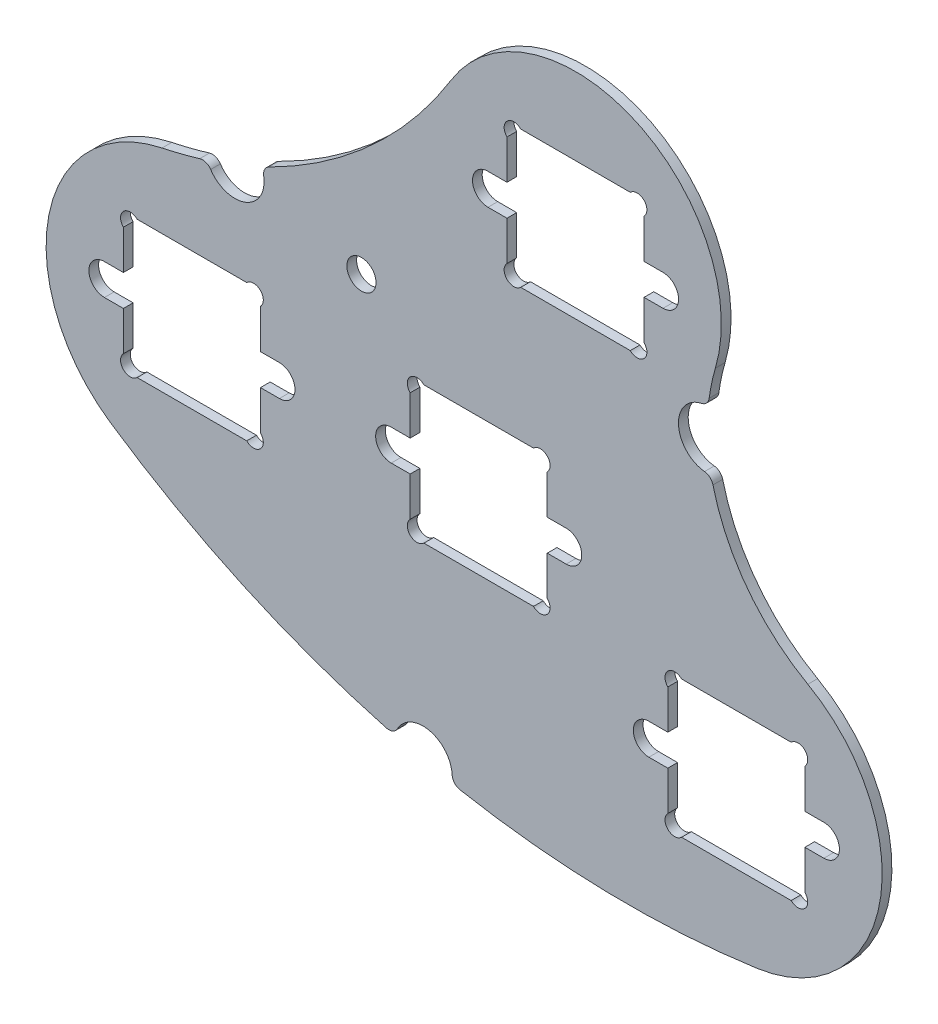
SolidWorks part; units mm, degrees
ref_plane "Front Plane" through (0, 0, 0) normal (0, 0, 1) x (1, 0, 0)
ref_plane "Top Plane" through (0, 0, 0) normal (0, 1, 0) x (1, 0, 0)
ref_plane "Right Plane" through (0, 0, 0) normal (1, 0, 0) x (0, 0, -1)
sketch "Sketch1" plane through (0, 0, 0) normal (0, 0, 1) x (1, 0, 0)
  line L0 (157.8919, 26.2701) -> (191.7747, 29.0915)
  line L1 (157.8919, 26.2701) -> (191.7747, 26.2701)
  line L2 (157.8919, 26.2701) -> (157.8919, 29.0915)
  line L3 (157.8919, 29.0915) -> (191.7747, 29.0915)
  line L4 (191.7747, 26.2701) -> (191.7747, 29.0915)
  line L5 (123.8919, 26.2701) -> (90.0092, 26.2701)
  line L6 (123.8919, 26.2701) -> (123.8919, 29.0915)
  line L7 (123.8919, 29.0915) -> (90.0092, 29.0915)
  line L8 (90.0092, 26.2701) -> (90.0092, 29.0915)
  line L9 (90.0092, 29.0915) -> (123.8919, 26.2701)
  line L10 (168.0919, 58.3601) -> (194.8735, 70.7292)
  line L11 (168.0919, 58.3601) -> (194.8735, 58.3601)
  line L12 (168.0919, 58.3601) -> (168.0919, 70.7292)
  line L13 (168.0919, 70.7292) -> (194.8735, 70.7292)
  line L14 (194.8735, 58.3601) -> (194.8735, 70.7292)
  line L15 (194.8735, 70.7292) -> (224.3587, 70.7292)
  line L16 (194.8735, 70.7292) -> (194.8735, 69.7923)
  line L17 (194.8735, 69.7923) -> (224.3587, 69.7923)
  line L18 (224.3587, 70.7292) -> (224.3587, 69.7923)
  line L19 (224.3587, 69.7923) -> (253.5106, 69.7923)
  line L20 (224.3587, 69.7923) -> (224.3587, 65.2742)
  line L21 (224.3587, 65.2742) -> (253.5106, 65.2742)
  line L22 (253.5106, 69.7923) -> (253.5106, 65.2742)
  line L23 (224.3587, 69.7923) -> (194.8735, 70.7292)
  line L24 (253.5106, 65.2742) -> (224.3587, 69.7923)
  line L25 (170.7502, 87.7401) -> (168.0919, 58.3601)
  line L26 (168.0919, 58.3601) -> (170.7502, 58.3601)
  line L27 (168.0919, 58.3601) -> (168.0919, 87.7401)
  line L28 (168.0919, 87.7401) -> (170.7502, 87.7401)
  line L29 (170.7502, 58.3601) -> (170.7502, 87.7401)
  line L30 (52.9966, 89.4705) -> (24.4119, 82.1791)
  line L31 (24.4119, 82.1791) -> (52.9966, 82.1791)
  line L32 (24.4119, 82.1791) -> (24.4119, 89.4705)
  line L33 (24.4119, 89.4705) -> (52.9966, 89.4705)
  line L34 (52.9966, 82.1791) -> (52.9966, 89.4705)
  line L35 (82.4966, 89.4705) -> (109.0019, 89.4705)
  line L36 (82.4966, 89.4705) -> (82.4966, 76.5201)
  line L37 (82.4966, 76.5201) -> (109.0019, 76.5201)
  line L38 (109.0019, 89.4705) -> (109.0019, 76.5201)
  line L39 (92.4554, 117.2387) -> (82.4966, 117.2387)
  line L40 (92.4554, 117.2387) -> (92.4554, 89.4705)
  line L41 (92.4554, 89.4705) -> (82.4966, 89.4705)
  line L42 (82.4966, 117.2387) -> (82.4966, 89.4705)
  line L43 (92.4554, 117.2387) -> (82.4966, 89.4705)
  line L44 (109.0019, 76.5201) -> (82.4966, 89.4705)
  circle A0 centre (123.8919, 26.2701) radius 14.25
  circle A1 centre (157.8919, 26.2701) radius 14.25
  circle A2 centre (90.0092, 29.0915) radius 14.25
  circle A3 centre (191.7747, 29.0915) radius 14.25
  circle A4 centre (82.4966, 89.4705) radius 11.25
  circle A5 centre (92.4554, 117.2387) radius 11.25
  circle A6 centre (52.9966, 89.4705) radius 11.25
  circle A7 centre (109.0019, 76.5201) radius 11.25
  circle A8 centre (24.4119, 82.1791) radius 11.25
  circle A9 centre (170.7502, 87.7401) radius 11.25
  circle A10 centre (168.0919, 58.3601) radius 11.25
  circle A11 centre (197.5318, 100.1092) radius 11.25
  circle A12 centre (194.8735, 70.7292) radius 11.25
  circle A13 centre (227.0169, 99.1723) radius 11.25
  circle A14 centre (224.3587, 69.7923) radius 11.25
  circle A15 centre (256.1689, 94.6541) radius 11.25
  circle A16 centre (253.5106, 65.2742) radius 11.25
  circle A17 centre (24.4119, 82.1791) radius 12
  circle A18 centre (52.9966, 89.4705) radius 12
  circle A19 centre (92.4554, 117.2387) radius 12
  circle A20 centre (82.4966, 89.4705) radius 12
  circle A21 centre (109.0019, 76.5201) radius 12
  circle A22 centre (168.0919, 58.3601) radius 12
  circle A23 centre (194.8735, 70.7292) radius 12
  circle A24 centre (224.3587, 69.7923) radius 12
  circle A25 centre (253.5106, 65.2742) radius 12
  circle A26 centre (256.1689, 94.6541) radius 12
  circle A27 centre (227.0169, 99.1723) radius 12
  circle A28 centre (197.5318, 100.1092) radius 12
  circle A29 centre (170.7502, 87.7401) radius 12
  circle A30 centre (191.7747, 29.0915) radius 15
  circle A31 centre (157.8919, 26.2701) radius 15
  circle A32 centre (123.8919, 26.2701) radius 15
  circle A33 centre (90.0092, 29.0915) radius 15
  circle A34 centre (173.429, 117.1182) radius 11.25
  circle A35 centre (173.429, 117.1182) radius 12
  dimension "D1" = 28.5
  dimension "D2" = 22.5
  dimension "D3" = 0.75
  dimension "D4" = 0.75
  dimension "D34" = 34
  dimension "D5" = 29.5
  dimension "D6" = 29.5
  dimension "D7" = 29.5
  dimension "D8" = 29.5
  dimension "D9" = 29.5
  dimension "D10" = 29.5
  dimension "D11" = 29.5
  dimension "D12" = 29.5
  dimension "D13" = 29.5
  dimension "D14" = 29.5
  dimension "D15" = 29.5
  dimension "D16" = 29.5
  dimension "D17" = 29.5
  dimension "D18" = 29.5
  dimension "D19" = 34
  dimension "D20" = 34
  dimension "D21" = 32.09
  dimension "D22" = 10.2
  dimension "D23" = 4.76
  dimension "D24" = 4.76
  dimension "D25" = 24.79
  dimension "D26" = 1.82
  dimension "D27" = 8.81
  dimension "D28" = 84.83
  dimension "D29" = 75.69
  dimension "D30" = 70.27
  dimension "D31" = 26.04
  dimension "D32" = 14.89
  dimension "D33" = 50.25
  dimension "D35" = 29.5
  dimension "D36" = 29.5
sketch "Sketch4" plane through (-30.2083, 20.075, 0) normal (0, 0, 1) x (0.9781, -0.2079, 0)
  line L0 (86.1706, 94.1917) -> (105.2206, 75.1417)
  line L1 (67.1206, 94.1917) -> (86.1706, 94.1917)
  line L2 (67.1206, 94.1917) -> (67.1206, 75.1417)
  line L3 (67.1206, 75.1417) -> (86.1706, 75.1417)
  line L4 (86.1706, 94.1917) -> (86.1706, 75.1417)
  line L5 (86.1706, 94.1917) -> (105.2206, 94.1917)
  line L6 (86.1706, 94.1917) -> (86.1706, 75.1417)
  line L7 (86.1706, 75.1417) -> (105.2206, 75.1417)
  line L8 (105.2206, 94.1917) -> (105.2206, 75.1417)
  line L9 (105.2206, 94.1917) -> (124.2706, 94.1917)
  line L10 (105.2206, 94.1917) -> (105.2206, 75.1417)
  line L11 (105.2206, 75.1417) -> (124.2706, 75.1417)
  line L12 (124.2706, 94.1917) -> (124.2706, 75.1417)
  line L13 (86.1706, 94.1917) -> (105.2206, 94.1917)
  line L14 (86.1706, 94.1917) -> (86.1706, 113.2417)
  line L15 (86.1706, 113.2417) -> (105.2206, 113.2417)
  line L16 (105.2206, 94.1917) -> (105.2206, 113.2417)
  line L17 (66.9585, 85.1784) -> (124.4326, 84.1551)
  point P14 (95.6956, 84.6667)
  point P15 (95.6956, 84.6667)
  dimension "D1" = 19.05
sketch "Sketch9" plane through (0, 0, 0) normal (0, 0, 1) x (1, 0, 0)
  line L1 (17.3619, 89.2291) -> (31.4619, 89.2291)
  line L2 (17.3619, 89.2291) -> (17.3619, 75.1291)
  line L3 (17.3619, 75.1291) -> (31.4619, 75.1291)
  line L4 (31.4619, 89.2291) -> (31.4619, 75.1291)
  line L5 (45.9466, 96.5205) -> (60.0466, 96.5205)
  line L6 (45.9466, 96.5205) -> (45.9466, 82.4205)
  line L7 (45.9466, 82.4205) -> (60.0466, 82.4205)
  line L8 (60.0466, 96.5205) -> (60.0466, 82.4205)
  line L9 (75.4466, 96.5205) -> (89.5466, 96.5205)
  line L10 (75.4466, 96.5205) -> (75.4466, 82.4205)
  line L11 (75.4466, 82.4205) -> (89.5466, 82.4205)
  line L12 (89.5466, 96.5205) -> (89.5466, 82.4205)
  line L13 (101.9519, 83.5701) -> (116.0519, 83.5701)
  line L14 (101.9519, 83.5701) -> (101.9519, 69.4701)
  line L15 (101.9519, 69.4701) -> (116.0519, 69.4701)
  line L16 (116.0519, 83.5701) -> (116.0519, 69.4701)
  line L17 (85.4054, 124.2887) -> (99.5054, 124.2887)
  line L18 (85.4054, 124.2887) -> (85.4054, 110.1887)
  line L19 (85.4054, 110.1887) -> (99.5054, 110.1887)
  line L20 (99.5054, 124.2887) -> (99.5054, 110.1887)
  line L21 (82.9592, 36.1415) -> (97.0592, 36.1415)
  line L22 (82.9592, 36.1415) -> (82.9592, 22.0415)
  line L23 (82.9592, 22.0415) -> (97.0592, 22.0415)
  line L24 (97.0592, 36.1415) -> (97.0592, 22.0415)
  line L25 (116.8419, 33.3201) -> (130.9419, 33.3201)
  line L26 (116.8419, 33.3201) -> (116.8419, 19.2201)
  line L27 (116.8419, 19.2201) -> (130.9419, 19.2201)
  line L28 (130.9419, 33.3201) -> (130.9419, 19.2201)
  line L29 (150.8419, 33.3201) -> (164.9419, 33.3201)
  line L30 (150.8419, 33.3201) -> (150.8419, 19.2201)
  line L31 (150.8419, 19.2201) -> (164.9419, 19.2201)
  line L32 (164.9419, 33.3201) -> (164.9419, 19.2201)
  line L33 (184.7247, 36.1415) -> (198.8247, 36.1415)
  line L34 (184.7247, 36.1415) -> (184.7247, 22.0415)
  line L35 (184.7247, 22.0415) -> (198.8247, 22.0415)
  line L36 (198.8247, 36.1415) -> (198.8247, 22.0415)
  line L37 (260.5606, 58.2242) -> (246.4606, 58.2242)
  line L38 (260.5606, 58.2242) -> (260.5606, 72.3242)
  line L39 (260.5606, 72.3242) -> (246.4606, 72.3242)
  line L40 (246.4606, 58.2242) -> (246.4606, 72.3242)
  line L41 (217.3087, 76.8423) -> (231.4087, 76.8423)
  line L42 (217.3087, 76.8423) -> (217.3087, 62.7423)
  line L43 (217.3087, 62.7423) -> (231.4087, 62.7423)
  line L44 (231.4087, 76.8423) -> (231.4087, 62.7423)
  line L45 (187.8235, 77.7792) -> (201.9235, 77.7792)
  line L46 (187.8235, 77.7792) -> (187.8235, 63.6792)
  line L47 (187.8235, 63.6792) -> (201.9235, 63.6792)
  line L48 (201.9235, 77.7792) -> (201.9235, 63.6792)
  line L49 (161.0419, 65.4101) -> (175.1419, 65.4101)
  line L50 (161.0419, 65.4101) -> (161.0419, 51.3101)
  line L51 (161.0419, 51.3101) -> (175.1419, 51.3101)
  line L52 (175.1419, 65.4101) -> (175.1419, 51.3101)
  line L53 (163.7002, 94.7901) -> (177.8002, 94.7901)
  line L54 (163.7002, 94.7901) -> (163.7002, 80.6901)
  line L55 (163.7002, 80.6901) -> (177.8002, 80.6901)
  line L56 (177.8002, 94.7901) -> (177.8002, 80.6901)
  line L57 (190.4818, 107.1592) -> (204.5818, 107.1592)
  line L58 (190.4818, 107.1592) -> (190.4818, 93.0592)
  line L59 (190.4818, 93.0592) -> (204.5818, 93.0592)
  line L60 (204.5818, 107.1592) -> (204.5818, 93.0592)
  line L61 (219.9669, 106.2223) -> (234.0669, 106.2223)
  line L62 (219.9669, 106.2223) -> (219.9669, 92.1223)
  line L63 (219.9669, 92.1223) -> (234.0669, 92.1223)
  line L64 (234.0669, 106.2223) -> (234.0669, 92.1223)
  line L65 (249.1189, 101.7041) -> (263.2189, 101.7041)
  line L66 (249.1189, 101.7041) -> (249.1189, 87.6041)
  line L67 (249.1189, 87.6041) -> (263.2189, 87.6041)
  line L68 (263.2189, 101.7041) -> (263.2189, 87.6041)
  line L69 (166.379, 124.1682) -> (180.479, 124.1682)
  line L70 (166.379, 124.1682) -> (166.379, 110.0682)
  line L71 (166.379, 110.0682) -> (180.479, 110.0682)
  line L72 (180.479, 124.1682) -> (180.479, 110.0682)
  point P72 (24.4119, 89.2291)
  point P74 (52.9966, 96.5205)
  point P76 (82.4966, 96.5205)
  point P78 (92.4554, 124.2887)
  point P80 (109.0019, 83.5701)
  point P82 (90.0092, 36.1415)
  point P84 (123.8919, 33.3201)
  point P86 (157.8919, 33.3201)
  point P88 (191.7747, 36.1415)
  point P90 (168.0919, 65.4101)
  point P92 (170.7502, 94.7901)
  point P94 (173.429, 124.1682)
  point P96 (197.5318, 107.1592)
  point P98 (227.0169, 106.2223)
  point P100 (256.1689, 101.7041)
  point P102 (194.8735, 77.7792)
  point P104 (224.3587, 76.8423)
  point P106 (253.5106, 72.3242)
  point P108 (17.3619, 82.1791)
  point P109 (45.9466, 89.4705)
  point P110 (75.4466, 89.4705)
  point P111 (101.9519, 76.5201)
  point P112 (85.4054, 117.2387)
  point P113 (82.9592, 29.0915)
  point P114 (116.8419, 26.2701)
  point P115 (150.8419, 26.2701)
  point P116 (184.7247, 29.0915)
  point P117 (0, 0)
  point P118 (161.0419, 58.3601)
  point P119 (187.8235, 70.7292)
  point P120 (217.3087, 69.7923)
  point P121 (246.4606, 65.2742)
  point P122 (163.7002, 87.7401)
  point P123 (190.4818, 100.1092)
  point P124 (219.9669, 99.1723)
  point P125 (249.1189, 94.6541)
  point P126 (166.379, 117.1182)
  dimension "D1" = 14.1
sketch "Sketch10" plane through (-22.0981, 19.3454, 0) normal (0, 0, 1) x (0.9781, -0.2079, 0)
  line L1 (61.5108, 90.7441) -> (75.6108, 90.7441)
  line L2 (61.5108, 90.7441) -> (61.5108, 76.6441)
  line L3 (61.5108, 76.6441) -> (75.6108, 76.6441)
  line L4 (75.6108, 90.7441) -> (75.6108, 76.6441)
  line L5 (80.5608, 90.7441) -> (94.6608, 90.7441)
  line L6 (80.5608, 90.7441) -> (80.5608, 76.6441)
  line L7 (80.5608, 76.6441) -> (94.6608, 76.6441)
  line L8 (94.6608, 90.7441) -> (94.6608, 76.6441)
  line L9 (99.6108, 90.7441) -> (113.7108, 90.7441)
  line L10 (99.6108, 90.7441) -> (99.6108, 76.6441)
  line L11 (99.6108, 76.6441) -> (113.7108, 76.6441)
  line L12 (113.7108, 90.7441) -> (113.7108, 76.6441)
  line L13 (80.5608, 109.7941) -> (94.6608, 109.7941)
  line L14 (80.5608, 109.7941) -> (80.5608, 95.6941)
  line L15 (80.5608, 95.6941) -> (94.6608, 95.6941)
  line L16 (94.6608, 109.7941) -> (94.6608, 95.6941)
  line L17 (50.5121, 89.6359) -> (53.4436, 75.8441) construction
  line L18 (59.0358, 93.2191) -> (78.0858, 93.2191) construction
  line L19 (78.0858, 112.2691) -> (97.1358, 112.2691) construction
  line L20 (97.1358, 93.2191) -> (116.1858, 93.2191) construction
  line L21 (78.0858, 93.2191) -> (78.0858, 112.2691) construction
  line L23 (59.0358, 93.2191) -> (59.0358, 74.1691) construction
  point P16 (75.6108, 83.6941)
  point P17 (94.6608, 83.6941)
  point P18 (113.7108, 83.6941)
  point P19 (87.6108, 90.7441)
  point P20 (87.6108, 109.7941)
  point P23 (68.5608, 90.7441)
  point P26 (68.5608, 93.2191)
  point P29 (87.6108, 112.2691)
  point P30 (106.6608, 90.7441)
  point P33 (106.6608, 93.2191)
  point P34 (80.5608, 102.7441)
  point P37 (78.0858, 102.7441)
  point P42 (59.0358, 83.6941)
  point P43 (61.5108, 83.6941)
sketch "Sketch14" plane through (0, 0, 0) normal (0, 0, 1) x (1, 0, 0)
  line L0 (165.1144, 80.6901) -> (163.7002, 82.1043)
  line L1 (163.7002, 93.3758) -> (165.1144, 94.7901)
  line L2 (177.8002, 93.3758) -> (176.386, 94.7901)
  line L3 (179.0648, 110.0682) -> (180.479, 111.4824)
  line L4 (166.379, 111.4824) -> (167.7932, 110.0682)
  line L5 (166.379, 122.754) -> (167.7932, 124.1682)
  line L6 (179.0648, 124.1682) -> (180.479, 122.754)
  line L7 (203.1676, 93.0592) -> (204.5818, 94.4734)
  line L8 (17.3619, 89.2291) -> (17.3619, 75.1291) construction
  line L9 (17.3619, 89.2291) -> (31.4619, 89.2291) construction
  line L10 (17.3619, 87.8149) -> (18.7761, 89.2291)
  line L11 (17.3619, 75.1291) -> (31.4619, 75.1291) construction
  line L12 (31.4619, 89.2291) -> (31.4619, 75.1291) construction
  line L13 (45.9466, 96.5205) -> (60.0466, 96.5205) construction
  line L14 (60.0466, 96.5205) -> (60.0466, 82.4205) construction
  line L15 (45.9466, 96.5205) -> (45.9466, 82.4205) construction
  line L16 (45.9466, 82.4205) -> (60.0466, 82.4205) construction
  line L17 (85.4054, 124.2887) -> (85.4054, 110.1887) construction
  line L18 (85.4054, 124.2887) -> (99.5054, 124.2887) construction
  line L19 (99.5054, 124.2887) -> (99.5054, 110.1887) construction
  line L20 (85.4054, 110.1887) -> (99.5054, 110.1887) construction
  line L21 (101.9519, 83.5701) -> (101.9519, 69.4701) construction
  line L22 (101.9519, 83.5701) -> (116.0519, 83.5701) construction
  line L23 (116.0519, 83.5701) -> (116.0519, 69.4701) construction
  line L24 (101.9519, 69.4701) -> (116.0519, 69.4701) construction
  line L25 (91.2712, 73.6044) -> (105.0631, 70.6729) construction
  line L26 (107.9947, 84.4647) -> (105.0631, 70.6729) construction
  line L27 (94.2028, 87.3963) -> (107.9947, 84.4647) construction
  line L28 (94.2028, 87.3963) -> (91.2712, 73.6044) construction
  line L29 (72.6375, 77.5651) -> (86.4294, 74.6336) construction
  line L30 (89.361, 88.4255) -> (86.4294, 74.6336) construction
  line L31 (75.5691, 91.357) -> (89.361, 88.4255) construction
  line L32 (75.5691, 91.357) -> (72.6375, 77.5651) construction
  line L33 (56.9354, 95.3177) -> (54.0038, 81.5259) construction
  line L34 (56.9354, 95.3177) -> (70.7273, 92.3862) construction
  line L35 (70.7273, 92.3862) -> (67.7957, 78.5943) construction
  line L36 (54.0038, 81.5259) -> (67.7957, 78.5943) construction
  line L37 (76.5983, 96.1988) -> (90.3901, 93.2673) construction
  line L38 (93.3217, 107.0592) -> (90.3901, 93.2673) construction
  line L39 (79.5298, 109.9907) -> (76.5983, 96.1988) construction
  line L40 (79.5298, 109.9907) -> (93.3217, 107.0592) construction
  line L41 (82.9592, 36.1415) -> (82.9592, 22.0415) construction
  line L42 (82.9592, 36.1415) -> (97.0592, 36.1415) construction
  line L43 (82.9592, 22.0415) -> (97.0592, 22.0415) construction
  line L44 (97.0592, 36.1415) -> (97.0592, 22.0415) construction
  line L45 (116.8419, 33.3201) -> (116.8419, 19.2201) construction
  line L46 (116.8419, 33.3201) -> (130.9419, 33.3201) construction
  line L47 (116.8419, 19.2201) -> (130.9419, 19.2201) construction
  line L48 (130.9419, 33.3201) -> (130.9419, 19.2201) construction
  line L49 (150.8419, 33.3201) -> (150.8419, 19.2201) construction
  line L50 (150.8419, 33.3201) -> (164.9419, 33.3201) construction
  line L51 (164.9419, 33.3201) -> (164.9419, 19.2201) construction
  line L52 (150.8419, 19.2201) -> (164.9419, 19.2201) construction
  line L53 (184.7247, 36.1415) -> (184.7247, 22.0415) construction
  line L54 (184.7247, 22.0415) -> (198.8247, 22.0415) construction
  line L55 (198.8247, 36.1415) -> (198.8247, 22.0415) construction
  line L56 (184.7247, 36.1415) -> (198.8247, 36.1415) construction
  line L57 (161.0419, 65.4101) -> (175.1419, 65.4101) construction
  line L58 (175.1419, 65.4101) -> (175.1419, 51.3101) construction
  line L59 (161.0419, 51.3101) -> (175.1419, 51.3101) construction
  line L60 (161.0419, 65.4101) -> (161.0419, 51.3101) construction
  line L61 (187.8235, 77.7792) -> (187.8235, 63.6792) construction
  line L62 (187.8235, 77.7792) -> (201.9235, 77.7792) construction
  line L63 (187.8235, 63.6792) -> (201.9235, 63.6792) construction
  line L64 (201.9235, 77.7792) -> (201.9235, 63.6792) construction
  line L65 (217.3087, 76.8423) -> (217.3087, 62.7423) construction
  line L66 (217.3087, 76.8423) -> (231.4087, 76.8423) construction
  line L67 (231.4087, 76.8423) -> (231.4087, 62.7423) construction
  line L68 (217.3087, 62.7423) -> (231.4087, 62.7423) construction
  line L69 (260.5606, 58.2242) -> (246.4606, 58.2242) construction
  line L70 (260.5606, 58.2242) -> (260.5606, 72.3242) construction
  line L71 (246.4606, 58.2242) -> (246.4606, 72.3242) construction
  line L72 (260.5606, 72.3242) -> (246.4606, 72.3242) construction
  line L73 (249.1189, 101.7041) -> (263.2189, 101.7041) construction
  line L74 (263.2189, 101.7041) -> (263.2189, 87.6041) construction
  line L75 (249.1189, 87.6041) -> (263.2189, 87.6041) construction
  line L76 (249.1189, 101.7041) -> (249.1189, 87.6041) construction
  line L77 (219.9669, 106.2223) -> (219.9669, 92.1223) construction
  line L78 (219.9669, 106.2223) -> (234.0669, 106.2223) construction
  line L79 (234.0669, 106.2223) -> (234.0669, 92.1223) construction
  line L80 (219.9669, 92.1223) -> (234.0669, 92.1223) construction
  line L81 (190.4818, 107.1592) -> (204.5818, 107.1592) construction
  line L82 (204.5818, 107.1592) -> (204.5818, 93.0592) construction
  line L83 (190.4818, 93.0592) -> (204.5818, 93.0592) construction
  line L84 (190.4818, 107.1592) -> (190.4818, 93.0592) construction
  line L85 (163.7002, 94.7901) -> (177.8002, 94.7901) construction
  line L86 (177.8002, 94.7901) -> (177.8002, 80.6901) construction
  line L87 (163.7002, 80.6901) -> (177.8002, 80.6901) construction
  line L88 (163.7002, 94.7901) -> (163.7002, 80.6901) construction
  line L89 (180.479, 124.1682) -> (180.479, 110.0682) construction
  line L90 (166.379, 110.0682) -> (180.479, 110.0682) construction
  line L91 (166.379, 124.1682) -> (166.379, 110.0682) construction
  line L92 (166.379, 124.1682) -> (180.479, 124.1682) construction
  line L93 (17.3619, 76.5433) -> (18.7761, 75.1291)
  line L94 (30.0477, 75.1291) -> (31.4619, 76.5433)
  line L95 (31.4619, 87.8149) -> (30.0477, 89.2291)
  line L96 (45.9466, 95.1063) -> (47.3608, 96.5205)
  line L97 (45.9466, 83.8347) -> (47.3608, 82.4205)
  line L98 (54.2979, 82.9092) -> (55.3871, 81.2318)
  line L99 (58.6323, 82.4205) -> (60.0466, 83.8347)
  line L100 (56.6413, 93.9344) -> (58.3187, 95.0237)
  line L101 (58.6323, 96.5205) -> (60.0466, 95.1063)
  line L102 (69.3439, 92.6802) -> (70.4332, 91.0029)
  line L103 (68.0897, 79.9776) -> (66.4124, 78.8883)
  line L104 (75.2751, 89.9737) -> (76.9524, 91.063)
  line L105 (72.9316, 78.9484) -> (74.0208, 77.2711)
  line L106 (85.0461, 74.9276) -> (86.7234, 76.0169)
  line L107 (89.0669, 87.0421) -> (87.9777, 88.7195)
  line L108 (89.0068, 93.5613) -> (90.6842, 94.6506)
  line L109 (76.8923, 97.5822) -> (77.9816, 95.9048)
  line L110 (91.9384, 107.3532) -> (93.0277, 105.6759)
  line L111 (79.2358, 108.6074) -> (80.9131, 109.6967)
  line L112 (85.4054, 111.6029) -> (86.8196, 110.1887)
  line L113 (98.0912, 110.1887) -> (99.5054, 111.6029)
  line L114 (98.0912, 124.2887) -> (99.5054, 122.8745)
  line L115 (85.4054, 122.8745) -> (86.8196, 124.2887)
  line L116 (93.9088, 86.013) -> (95.5861, 87.1023)
  line L117 (91.5653, 74.9877) -> (92.6546, 73.3104)
  line L118 (103.6798, 70.9669) -> (105.3572, 72.0562)
  line L119 (106.6114, 84.7588) -> (107.7006, 83.0814)
  line L120 (101.9519, 82.1559) -> (103.3662, 83.5701)
  line L121 (101.9519, 70.8843) -> (103.3662, 69.4701)
  line L122 (114.6377, 69.4701) -> (116.0519, 70.8843)
  line L123 (116.0519, 82.1559) -> (114.6377, 83.5701)
  line L124 (82.9592, 34.7272) -> (84.3734, 36.1415)
  line L125 (82.9592, 23.4557) -> (84.3734, 22.0415)
  line L126 (95.645, 22.0415) -> (97.0592, 23.4557)
  line L127 (97.0592, 34.7272) -> (95.645, 36.1415)
  line L128 (116.8419, 31.9059) -> (118.2562, 33.3201)
  line L129 (116.8419, 20.6343) -> (118.2562, 19.2201)
  line L130 (129.5277, 19.2201) -> (130.9419, 20.6343)
  line L131 (130.9419, 31.9059) -> (129.5277, 33.3201)
  line L132 (150.8419, 31.9059) -> (152.2562, 33.3201)
  line L133 (150.8419, 20.6343) -> (152.2562, 19.2201)
  line L134 (163.5277, 19.2201) -> (164.9419, 20.6343)
  line L135 (164.9419, 31.9059) -> (163.5277, 33.3201)
  line L136 (184.7247, 34.7272) -> (186.1389, 36.1415)
  line L137 (184.7247, 23.4557) -> (186.1389, 22.0415)
  line L138 (197.4105, 22.0415) -> (198.8247, 23.4557)
  line L139 (198.8247, 34.7272) -> (197.4105, 36.1415)
  line L140 (173.7277, 51.3101) -> (175.1419, 52.7243)
  line L141 (161.0419, 52.7243) -> (162.4562, 51.3101)
  line L142 (161.0419, 63.9959) -> (162.4562, 65.4101)
  line L143 (173.7277, 65.4101) -> (175.1419, 63.9959)
  line L144 (187.8235, 65.0934) -> (189.2378, 63.6792)
  line L145 (200.5093, 63.6792) -> (201.9235, 65.0934)
  line L146 (200.5093, 77.7792) -> (201.9235, 76.365)
  line L147 (187.8235, 76.365) -> (189.2378, 77.7792)
  line L148 (176.386, 80.6901) -> (177.8002, 82.1043)
  line L149 (204.5818, 105.745) -> (203.1676, 107.1592)
  line L150 (191.896, 107.1592) -> (190.4818, 105.745)
  line L151 (190.4818, 94.4734) -> (191.896, 93.0592)
  line L152 (219.9669, 104.8081) -> (221.3812, 106.2223)
  line L153 (232.6527, 106.2223) -> (234.0669, 104.8081)
  line L154 (234.0669, 93.5365) -> (232.6527, 92.1223)
  line L155 (219.9669, 93.5365) -> (221.3812, 92.1223)
  line L156 (229.9944, 76.8423) -> (231.4087, 75.4281)
  line L157 (217.3087, 75.4281) -> (218.7229, 76.8423)
  line L158 (217.3087, 64.1565) -> (218.7229, 62.7423)
  line L159 (229.9944, 62.7423) -> (231.4087, 64.1565)
  line L160 (259.1464, 72.3242) -> (260.5606, 70.9099)
  line L161 (246.4606, 70.9099) -> (247.8748, 72.3242)
  line L162 (259.1464, 58.2242) -> (260.5606, 59.6384)
  line L163 (247.8748, 58.2242) -> (246.4606, 59.6384)
  line L164 (261.8047, 87.6041) -> (263.2189, 89.0183)
  line L165 (249.1189, 89.0183) -> (250.5331, 87.6041)
  line L166 (249.1189, 100.2899) -> (250.5331, 101.7041)
  line L167 (261.8047, 101.7041) -> (263.2189, 100.2899)
  line L168 (75.4466, 96.5205) -> (75.4466, 82.4205) construction
  line L169 (75.4466, 96.5205) -> (89.5466, 96.5205) construction
  line L170 (89.5466, 96.5205) -> (89.5466, 82.4205) construction
  line L171 (75.4466, 82.4205) -> (89.5466, 82.4205) construction
  line L172 (76.8608, 96.5205) -> (75.4466, 95.1063)
  line L173 (88.1323, 96.5205) -> (89.5466, 95.1063)
  line L174 (89.5466, 83.8347) -> (88.1323, 82.4205)
  line L175 (75.4466, 83.8347) -> (76.8608, 82.4205)
  arc A0 (17.3619, 87.8149) -> (18.7761, 89.2291) centre (18.069, 88.522) cw
  arc A1 (18.7761, 75.1291) -> (17.3619, 76.5433) centre (18.069, 75.8362) cw
  arc A2 (31.4619, 76.5433) -> (30.0477, 75.1291) centre (30.7548, 75.8362) cw
  arc A3 (30.0477, 89.2291) -> (31.4619, 87.8149) centre (30.7548, 88.522) cw
  arc A4 (58.6323, 96.5205) -> (60.0466, 95.1063) centre (59.3394, 95.8134) cw
  arc A5 (45.9466, 95.1063) -> (47.3608, 96.5205) centre (46.6537, 95.8134) cw
  arc A6 (47.3608, 82.4205) -> (45.9466, 83.8347) centre (46.6537, 83.1276) cw
  arc A7 (60.0466, 83.8347) -> (58.6323, 82.4205) centre (59.3394, 83.1276) cw
  arc A8 (85.4054, 122.8745) -> (86.8196, 124.2887) centre (86.1125, 123.5816) cw
  arc A9 (98.0912, 124.2887) -> (99.5054, 122.8745) centre (98.7983, 123.5816) cw
  arc A10 (99.5054, 111.6029) -> (98.0912, 110.1887) centre (98.7983, 110.8958) cw
  arc A11 (85.4054, 111.6029) -> (86.8196, 110.1887) centre (86.1125, 110.8958) ccw
  arc A12 (101.9519, 82.1559) -> (103.3662, 83.5701) centre (102.6591, 82.863) cw
  arc A13 (114.6377, 83.5701) -> (116.0519, 82.1559) centre (115.3448, 82.863) cw
  arc A14 (116.0519, 70.8843) -> (114.6377, 69.4701) centre (115.3448, 70.1772) cw
  arc A15 (101.9519, 70.8843) -> (103.3662, 69.4701) centre (102.6591, 70.1772) ccw
  arc A16 (103.6798, 70.9669) -> (105.3572, 72.0562) centre (104.5185, 71.5115) ccw
  arc A17 (106.6114, 84.7588) -> (107.7006, 83.0814) centre (107.156, 83.9201) cw
  arc A18 (93.9088, 86.013) -> (95.5861, 87.1023) centre (94.7474, 86.5576) cw
  arc A19 (91.5653, 74.9877) -> (92.6546, 73.3104) centre (92.1099, 74.1491) ccw
  arc A20 (85.0461, 74.9276) -> (86.7234, 76.0169) centre (85.8848, 75.4722) ccw
  arc A21 (87.9777, 88.7195) -> (89.0669, 87.0421) centre (88.5223, 87.8808) cw
  arc A22 (75.2751, 89.9737) -> (76.9524, 91.063) centre (76.1137, 90.5183) cw
  arc A23 (72.9316, 78.9484) -> (74.0208, 77.2711) centre (73.4762, 78.1098) ccw
  arc A24 (56.6413, 93.9344) -> (58.3187, 95.0237) centre (57.48, 94.4791) cw
  arc A25 (69.3439, 92.6802) -> (70.4332, 91.0029) centre (69.8886, 91.8415) cw
  arc A26 (68.0897, 79.9776) -> (66.4124, 78.8883) centre (67.2511, 79.433) cw
  arc A27 (54.2979, 82.9092) -> (55.3871, 81.2318) centre (54.8425, 82.0705) ccw
  arc A28 (89.0068, 93.5613) -> (90.6842, 94.6506) centre (89.8455, 94.106) ccw
  arc A29 (76.8923, 97.5822) -> (77.9816, 95.9048) centre (77.4369, 96.7435) ccw
  arc A30 (79.2358, 108.6074) -> (80.9131, 109.6967) centre (80.0744, 109.1521) cw
  arc A31 (91.9384, 107.3532) -> (93.0277, 105.6759) centre (92.483, 106.5145) cw
  arc A32 (82.9592, 34.7272) -> (84.3734, 36.1415) centre (83.6663, 35.4344) cw
  arc A33 (82.9592, 23.4557) -> (84.3734, 22.0415) centre (83.6663, 22.7486) ccw
  arc A34 (95.645, 22.0415) -> (97.0592, 23.4557) centre (96.3521, 22.7486) ccw
  arc A35 (95.645, 36.1415) -> (97.0592, 34.7272) centre (96.3521, 35.4344) cw
  arc A36 (116.8419, 31.9059) -> (118.2562, 33.3201) centre (117.5491, 32.613) cw
  arc A37 (116.8419, 20.6343) -> (118.2562, 19.2201) centre (117.5491, 19.9272) ccw
  arc A38 (129.5277, 19.2201) -> (130.9419, 20.6343) centre (130.2348, 19.9272) ccw
  arc A39 (129.5277, 33.3201) -> (130.9419, 31.9059) centre (130.2348, 32.613) cw
  arc A40 (150.8419, 31.9059) -> (152.2562, 33.3201) centre (151.5491, 32.613) cw
  arc A41 (163.5277, 33.3201) -> (164.9419, 31.9059) centre (164.2348, 32.613) cw
  arc A42 (164.9419, 20.6343) -> (163.5277, 19.2201) centre (164.2348, 19.9272) cw
  arc A43 (150.8419, 20.6343) -> (152.2562, 19.2201) centre (151.5491, 19.9272) ccw
  arc A44 (184.7247, 23.4557) -> (186.1389, 22.0415) centre (185.4318, 22.7486) ccw
  arc A45 (197.4105, 22.0415) -> (198.8247, 23.4557) centre (198.1176, 22.7486) ccw
  arc A46 (197.4105, 36.1415) -> (198.8247, 34.7272) centre (198.1176, 35.4344) cw
  arc A47 (184.7247, 34.7272) -> (186.1389, 36.1415) centre (185.4318, 35.4344) cw
  arc A48 (173.7277, 65.4101) -> (175.1419, 63.9959) centre (174.4348, 64.703) cw
  arc A49 (175.1419, 52.7243) -> (173.7277, 51.3101) centre (174.4348, 52.0172) cw
  arc A50 (161.0419, 52.7243) -> (162.4562, 51.3101) centre (161.7491, 52.0172) ccw
  arc A51 (161.0419, 63.9959) -> (162.4562, 65.4101) centre (161.7491, 64.703) cw
  arc A52 (187.8235, 76.365) -> (189.2378, 77.7792) centre (188.5306, 77.0721) cw
  arc A53 (187.8235, 65.0934) -> (189.2378, 63.6792) centre (188.5306, 64.3863) ccw
  arc A54 (200.5093, 63.6792) -> (201.9235, 65.0934) centre (201.2164, 64.3863) ccw
  arc A55 (200.5093, 77.7792) -> (201.9235, 76.365) centre (201.2164, 77.0721) cw
  arc A56 (217.3087, 75.4281) -> (218.7229, 76.8423) centre (218.0158, 76.1352) cw
  arc A57 (229.9944, 76.8423) -> (231.4087, 75.4281) centre (230.7016, 76.1352) cw
  arc A58 (231.4087, 64.1565) -> (229.9944, 62.7423) centre (230.7016, 63.4494) cw
  arc A59 (217.3087, 64.1565) -> (218.7229, 62.7423) centre (218.0158, 63.4494) ccw
  arc A60 (259.1464, 58.2242) -> (260.5606, 59.6384) centre (259.8535, 58.9313) ccw
  arc A61 (246.4606, 59.6384) -> (247.8748, 58.2242) centre (247.1677, 58.9313) ccw
  arc A62 (246.4606, 70.9099) -> (247.8748, 72.3242) centre (247.1677, 71.617) cw
  arc A63 (259.1464, 72.3242) -> (260.5606, 70.9099) centre (259.8535, 71.617) cw
  arc A64 (261.8047, 101.7041) -> (263.2189, 100.2899) centre (262.5118, 100.997) cw
  arc A65 (263.2189, 89.0183) -> (261.8047, 87.6041) centre (262.5118, 88.3112) cw
  arc A66 (250.5331, 87.6041) -> (249.1189, 89.0183) centre (249.826, 88.3112) cw
  arc A67 (249.1189, 100.2899) -> (250.5331, 101.7041) centre (249.826, 100.997) cw
  arc A68 (219.9669, 104.8081) -> (221.3812, 106.2223) centre (220.674, 105.5152) cw
  arc A69 (232.6527, 106.2223) -> (234.0669, 104.8081) centre (233.3598, 105.5152) cw
  arc A70 (234.0669, 93.5365) -> (232.6527, 92.1223) centre (233.3598, 92.8294) cw
  arc A71 (221.3812, 92.1223) -> (219.9669, 93.5365) centre (220.674, 92.8294) cw
  arc A72 (203.1676, 107.1592) -> (204.5818, 105.745) centre (203.8747, 106.4521) cw
  arc A73 (204.5818, 94.4734) -> (203.1676, 93.0592) centre (203.8747, 93.7663) cw
  arc A74 (191.896, 93.0592) -> (190.4818, 94.4734) centre (191.1889, 93.7663) cw
  arc A75 (190.4818, 105.745) -> (191.896, 107.1592) centre (191.1889, 106.4521) cw
  arc A76 (176.386, 94.7901) -> (177.8002, 93.3758) centre (177.0931, 94.0829) cw
  arc A77 (177.8002, 82.1043) -> (176.386, 80.6901) centre (177.0931, 81.3972) cw
  arc A78 (165.1144, 80.6901) -> (163.7002, 82.1043) centre (164.4073, 81.3972) cw
  arc A79 (163.7002, 93.3758) -> (165.1144, 94.7901) centre (164.4073, 94.0829) cw
  arc A80 (180.479, 111.4824) -> (179.0648, 110.0682) centre (179.7719, 110.7753) cw
  arc A81 (167.7932, 110.0682) -> (166.379, 111.4824) centre (167.0861, 110.7753) cw
  arc A82 (179.0648, 124.1682) -> (180.479, 122.754) centre (179.7719, 123.4611) cw
  arc A83 (166.379, 122.754) -> (167.7932, 124.1682) centre (167.0861, 123.4611) cw
  arc A84 (75.4466, 95.1063) -> (76.8608, 96.5205) centre (76.1537, 95.8134) cw
  arc A85 (88.1323, 96.5205) -> (89.5466, 95.1063) centre (88.8394, 95.8134) cw
  arc A86 (89.5466, 83.8347) -> (88.1323, 82.4205) centre (88.8394, 83.1276) cw
  arc A87 (76.8608, 82.4205) -> (75.4466, 83.8347) centre (76.1537, 83.1276) cw
  dimension "D1" = 45
  dimension "D2" = 1
  dimension "D71" = 45
  dimension "D3" = 45
  dimension "D4" = 45
  dimension "D5" = 45
  dimension "D6" = 45
  dimension "D7" = 45
  dimension "D8" = 45
  dimension "D9" = 45
  dimension "D10" = 45
  dimension "D11" = 45
  dimension "D12" = 45
  dimension "D13" = 45
  dimension "D14" = 45
  dimension "D15" = 45
  dimension "D16" = 45
  dimension "D17" = 45
  dimension "D18" = 45
  dimension "D19" = 45
  dimension "D20" = 45
  dimension "D21" = 45
  dimension "D22" = 45
  dimension "D23" = 45
  dimension "D24" = 45
  dimension "D25" = 45
  dimension "D26" = 45
  dimension "D27" = 45
  dimension "D28" = 45
  dimension "D29" = 45
  dimension "D30" = 45
  dimension "D31" = 45
  dimension "D32" = 45
  dimension "D33" = 45
  dimension "D34" = 45
  dimension "D35" = 45
  dimension "D36" = 45
  dimension "D37" = 45
  dimension "D38" = 45
  dimension "D39" = 45
  dimension "D40" = 45
  dimension "D41" = 45
  dimension "D42" = 45
  dimension "D43" = 45
  dimension "D44" = 45
  dimension "D45" = 45
  dimension "D46" = 45
  dimension "D47" = 45
  dimension "D48" = 45
  dimension "D49" = 45
  dimension "D50" = 45
  dimension "D51" = 45
  dimension "D52" = 45
  dimension "D53" = 45
  dimension "D54" = 45
  dimension "D55" = 45
  dimension "D56" = 45
  dimension "D57" = 45
  dimension "D58" = 45
  dimension "D59" = 45
  dimension "D60" = 45
  dimension "D61" = 45
  dimension "D62" = 45
  dimension "D63" = 45
  dimension "D64" = 45
  dimension "D65" = 45
  dimension "D66" = 45
  dimension "D67" = 45
  dimension "D68" = 45
  dimension "D69" = 45
  dimension "D70" = 45
  dimension "D72" = 45
  dimension "D73" = 45
  dimension "D74" = 45
  dimension "D75" = 45
  dimension "D76" = 45
  dimension "D77" = 45
  dimension "D78" = 45
  dimension "D79" = 45
  dimension "D80" = 45
  dimension "D81" = 45
  dimension "D82" = 45
  dimension "D83" = 45
  dimension "D84" = 45
  dimension "D85" = 45
  dimension "D86" = 45
  dimension "D87" = 45
  dimension "D88" = 45
  dimension "D89" = 45
sketch "Sketch16" plane through (0, 0, 0) normal (0, 0, 1) x (1, 0, 0)
  line L0 (81.0092, 30.6915) -> (99.0092, 30.6915)
  line L5 (17.3619, 89.2291) -> (17.3619, 75.1291) construction
  line L6 (81.0092, 30.6915) -> (81.0092, 27.4915)
  line L7 (17.3619, 75.1291) -> (31.4619, 75.1291) construction
  line L8 (15.4119, 83.7791) -> (33.4119, 83.7791)
  line L9 (15.4119, 83.7791) -> (15.4119, 80.5791)
  line L10 (15.4119, 80.5791) -> (33.4119, 80.5791)
  line L11 (33.4119, 83.7791) -> (33.4119, 80.5791)
  line L12 (81.0092, 27.4915) -> (99.0092, 27.4915)
  line L13 (99.0092, 30.6915) -> (99.0092, 27.4915)
  line L14 (114.8919, 27.8701) -> (132.8919, 27.8701)
  line L15 (114.8919, 27.8701) -> (114.8919, 24.6701)
  line L16 (114.8919, 24.6701) -> (132.8919, 24.6701)
  line L17 (132.8919, 27.8701) -> (132.8919, 24.6701)
  line L18 (148.8919, 27.8701) -> (166.8919, 27.8701)
  line L19 (148.8919, 27.8701) -> (148.8919, 24.6701)
  line L20 (148.8919, 24.6701) -> (166.8919, 24.6701)
  line L21 (166.8919, 27.8701) -> (166.8919, 24.6701)
  line L22 (182.7747, 30.6915) -> (200.7747, 30.6915)
  line L23 (182.7747, 30.6915) -> (182.7747, 27.4915)
  line L24 (182.7747, 27.4915) -> (200.7747, 27.4915)
  line L25 (200.7747, 30.6915) -> (200.7747, 27.4915)
  line L26 (43.9966, 91.0705) -> (61.9966, 91.0705)
  line L27 (43.9966, 91.0705) -> (43.9966, 87.8705)
  line L28 (43.9966, 87.8705) -> (61.9966, 87.8705)
  line L29 (61.9966, 91.0705) -> (61.9966, 87.8705)
  line L30 (73.4966, 91.0705) -> (91.4966, 91.0705)
  line L31 (73.4966, 91.0705) -> (73.4966, 87.8705)
  line L32 (73.4966, 87.8705) -> (91.4966, 87.8705)
  line L33 (91.4966, 91.0705) -> (91.4966, 87.8705)
  line L34 (100.0019, 78.1201) -> (118.0019, 78.1201)
  line L35 (100.0019, 78.1201) -> (100.0019, 74.9201)
  line L36 (100.0019, 74.9201) -> (118.0019, 74.9201)
  line L37 (118.0019, 78.1201) -> (118.0019, 74.9201)
  line L38 (83.4554, 118.8387) -> (101.4554, 118.8387)
  line L39 (83.4554, 118.8387) -> (83.4554, 115.6387)
  line L40 (83.4554, 115.6387) -> (101.4554, 115.6387)
  line L41 (101.4554, 118.8387) -> (101.4554, 115.6387)
  line L42 (164.429, 118.7182) -> (182.429, 118.7182)
  line L43 (164.429, 118.7182) -> (164.429, 115.5182)
  line L44 (164.429, 115.5182) -> (182.429, 115.5182)
  line L45 (182.429, 118.7182) -> (182.429, 115.5182)
  line L46 (161.7502, 89.3401) -> (179.7502, 89.3401)
  line L47 (161.7502, 89.3401) -> (161.7502, 86.1401)
  line L48 (161.7502, 86.1401) -> (179.7502, 86.1401)
  line L49 (179.7502, 89.3401) -> (179.7502, 86.1401)
  line L50 (188.5318, 101.7092) -> (206.5318, 101.7092)
  line L51 (188.5318, 101.7092) -> (188.5318, 98.5092)
  line L52 (188.5318, 98.5092) -> (206.5318, 98.5092)
  line L53 (206.5318, 101.7092) -> (206.5318, 98.5092)
  line L54 (159.0919, 59.9601) -> (177.0919, 59.9601)
  line L55 (159.0919, 59.9601) -> (159.0919, 56.7601)
  line L56 (159.0919, 56.7601) -> (177.0919, 56.7601)
  line L57 (177.0919, 59.9601) -> (177.0919, 56.7601)
  line L58 (185.8735, 72.3292) -> (203.8735, 72.3292)
  line L59 (185.8735, 72.3292) -> (185.8735, 69.1292)
  line L60 (185.8735, 69.1292) -> (203.8735, 69.1292)
  line L61 (203.8735, 72.3292) -> (203.8735, 69.1292)
  line L62 (218.0169, 100.7723) -> (236.0169, 100.7723)
  line L63 (218.0169, 100.7723) -> (218.0169, 97.5723)
  line L64 (218.0169, 97.5723) -> (236.0169, 97.5723)
  line L65 (236.0169, 100.7723) -> (236.0169, 97.5723)
  line L66 (215.3587, 71.3923) -> (233.3587, 71.3923)
  line L67 (215.3587, 71.3923) -> (215.3587, 68.1923)
  line L68 (215.3587, 68.1923) -> (233.3587, 68.1923)
  line L69 (233.3587, 71.3923) -> (233.3587, 68.1923)
  line L70 (247.1689, 96.2541) -> (265.1689, 96.2541)
  line L71 (247.1689, 96.2541) -> (247.1689, 93.0541)
  line L72 (247.1689, 93.0541) -> (265.1689, 93.0541)
  line L73 (265.1689, 96.2541) -> (265.1689, 93.0541)
  line L74 (244.5106, 66.8742) -> (262.5106, 66.8742)
  line L75 (244.5106, 66.8742) -> (244.5106, 63.6742)
  line L76 (244.5106, 63.6742) -> (262.5106, 63.6742)
  line L77 (262.5106, 66.8742) -> (262.5106, 63.6742)
  circle A0 centre (15.4119, 82.1791) radius 1.6
  circle A1 centre (33.4119, 82.1791) radius 1.6
  circle A2 centre (81.0092, 29.0915) radius 1.6
  circle A3 centre (99.0092, 29.0915) radius 1.6
  circle A4 centre (114.8919, 26.2701) radius 1.6
  circle A5 centre (132.8919, 26.2701) radius 1.6
  circle A6 centre (148.8919, 26.2701) radius 1.6
  circle A7 centre (166.8919, 26.2701) radius 1.6
  circle A8 centre (182.7747, 29.0915) radius 1.6
  circle A9 centre (200.7747, 29.0915) radius 1.6
  circle A10 centre (43.9966, 89.4705) radius 1.6
  circle A11 centre (61.9966, 89.4705) radius 1.6
  circle A12 centre (73.4966, 89.4705) radius 1.6
  circle A13 centre (91.4966, 89.4705) radius 1.6
  circle A14 centre (100.0019, 76.5201) radius 1.6
  circle A15 centre (118.0019, 76.5201) radius 1.6
  circle A16 centre (83.4554, 117.2387) radius 1.6
  circle A17 centre (101.4554, 117.2387) radius 1.6
  circle A18 centre (164.429, 117.1182) radius 1.6
  circle A19 centre (182.429, 117.1182) radius 1.6
  circle A20 centre (161.7502, 87.7401) radius 1.6
  circle A21 centre (179.7502, 87.7401) radius 1.6
  circle A22 centre (188.5318, 100.1092) radius 1.6
  circle A23 centre (206.5318, 100.1092) radius 1.6
  circle A24 centre (159.0919, 58.3601) radius 1.6
  circle A25 centre (177.0919, 58.3601) radius 1.6
  circle A26 centre (185.8735, 70.7292) radius 1.6
  circle A27 centre (203.8735, 70.7292) radius 1.6
  circle A28 centre (218.0169, 99.1723) radius 1.6
  circle A29 centre (236.0169, 99.1723) radius 1.6
  circle A30 centre (215.3587, 69.7923) radius 1.6
  circle A31 centre (233.3587, 69.7923) radius 1.6
  circle A32 centre (247.1689, 94.6541) radius 1.6
  circle A33 centre (265.1689, 94.6541) radius 1.6
  circle A34 centre (244.5106, 65.2742) radius 1.6
  circle A35 centre (262.5106, 65.2742) radius 1.6
  point P2 (24.4119, 75.1291)
  point P6 (17.3619, 82.1791)
  point P14 (24.4119, 80.5791)
  point P53 (90.0092, 30.6915)
  point P57 (123.8919, 27.8701)
  point P60 (157.8919, 27.8701)
  point P63 (191.7747, 30.6915)
  point P73 (52.9966, 91.0705)
  point P83 (82.4966, 91.0705)
  point P93 (109.0019, 78.1201)
  point P103 (92.4554, 118.8387)
  point P113 (173.429, 118.7182)
  point P123 (170.7502, 89.3401)
  point P133 (197.5318, 101.7092)
  point P143 (168.0919, 59.9601)
  point P153 (194.8735, 72.3292)
  point P163 (227.0169, 100.7723)
  point P173 (224.3587, 71.3923)
  point P183 (256.1689, 96.2541)
  point P193 (253.5106, 66.8742)
  dimension "D1" = 3.2
  dimension "D2" = 18
sketch "Sketch8" plane through (0, 0, 0) normal (0, 0, 1) x (1, 0, 0)
  line L0 (52.2844, 74.6389) -> (82.4966, 89.4705)
  line L1 (86.9403, 110.9459) -> (79.0189, 73.6784)
  line L2 (77.6235, 112.9262) -> (96.2572, 108.9655) construction
  line L3 (69.702, 75.6588) -> (88.3357, 71.6981) construction
  line L4 (53.3861, 72.3947) -> (55.5425, 73.4534)
  line L5 (99.6829, 63.2465) -> (101.1557, 61.3487)
  line L6 (103.1308, 62.8814) -> (82.4966, 89.4705)
  line L8 (73.6628, 94.2925) -> (77.6235, 112.9262) construction
  line L9 (55.029, 98.2532) -> (73.6628, 94.2925) construction
  line L13 (93.9017, 130.158) -> (94.0202, 130.4883)
  line L14 (99.5495, 128.1325) -> (99.6679, 128.4628)
  line L16 (99.4417, 62.7418) -> (100.7607, 61.0421)
  line L17 (55.5377, 72.894) -> (53.6064, 71.9459)
  line L19 (82.4966, 89.4705) -> (96.8441, 129.4755)
  circle A1 centre (57.4203, 106.4022) radius 2.5
  circle A2 centre (106.0456, 106.2134) radius 2.5
  circle A3 centre (76.7673, 63.0854) radius 2.5
  circle A4 centre (52.9966, 89.4705) radius 13
  circle A6 centre (92.4554, 117.2387) radius 13
  circle A7 centre (109.0019, 76.5201) radius 13
  circle A8 centre (82.4966, 89.4705) radius 25
  arc A10 (50.3337, 102.1949) -> (81.377, 124.0408) centre (40.5107, 149.1329) ccw
  circle A11 centre (103.1308, 62.8814) radius 2.5
  circle A12 centre (52.2844, 74.6389) radius 2.5
  circle A13 centre (96.8441, 129.4755) radius 2.5
  circle A14 centre (52.2844, 74.6389) radius 3
  circle A15 centre (103.1308, 62.8814) radius 3
  circle A16 centre (96.8441, 129.4755) radius 3
  arc A17 (104.9258, 113.5659) -> (115.3756, 87.8504) centre (126.3001, 107.2707) ccw
  arc A18 (45.7038, 78.7088) -> (110.8301, 63.6492) centre (97.7768, 155.5511) ccw
  circle A19 centre (92.4554, 117.2387) radius 15
  circle A20 centre (109.0019, 76.5201) radius 15
  circle A21 centre (52.9966, 89.4705) radius 15
  circle A22 centre (82.4966, 89.4705) radius 27
  arc A23 (44.5818, 77.0531) -> (111.1113, 61.6691) centre (97.7768, 155.5511) ccw
  arc A24 (49.924, 104.1525) -> (79.6727, 125.0873) centre (40.5107, 149.1329) ccw
  arc A25 (106.8443, 113.0008) -> (116.3562, 89.5935) centre (126.3001, 107.2707) ccw
  circle A26 centre (52.9966, 89.4705) radius 12.5
  circle A27 centre (109.0019, 76.5201) radius 12.5
  circle A28 centre (92.4554, 117.2387) radius 12.5
  circle A29 centre (82.4966, 89.4705) radius 24.5
  arc A30 (104.4462, 113.7071) -> (115.1305, 87.4146) centre (126.3001, 107.2707) ccw
  arc A31 (110.7597, 64.1443) -> (45.9842, 79.1227) centre (97.7768, 155.5511) cw
  arc A32 (50.4361, 101.7055) -> (81.8031, 123.7792) centre (40.5107, 149.1329) ccw
  circle A33 centre (52.9966, 89.4705) radius 15.5
  circle A34 centre (109.0019, 76.5201) radius 15.5
  circle A35 centre (92.4554, 117.2387) radius 15.5
  circle A36 centre (82.4966, 89.4705) radius 27.5
  arc A37 (107.3239, 112.8596) -> (116.6013, 90.0293) centre (126.3001, 107.2707) ccw
  arc A38 (111.1816, 61.1741) -> (44.3013, 76.6392) centre (97.7768, 155.5511) cw
  arc A39 (49.8216, 104.6419) -> (79.2466, 125.349) centre (40.5107, 149.1329) ccw
  circle A40 centre (106.0456, 106.2134) radius 3
  circle A41 centre (76.7673, 63.0854) radius 3
  circle A42 centre (57.4203, 106.4022) radius 3
  circle A43 centre (70.4353, 103.1572) radius 2.5
  dimension "D3" = 26
  dimension "D4" = 5
  dimension "D7" = 6
  dimension "D8" = 50
  dimension "D1" = 2
  dimension "D2" = 2
  dimension "D5" = 0.5
  dimension "D6" = 0.5
  dimension "D9" = 0.5
  dimension "D10" = 0.5
  dimension "D11" = 5
  dimension "D12" = 8
sketch "Sketch2" plane through (0, 0, 0) normal (0, 0, 1) x (1, 0, 0)
  line L0 (30.4119, 134.2387) -> (8.4119, 112.2387)
  line L1 (16.4119, 134.2387) -> (264.1689, 134.2387)
  line L2 (8.4119, 126.2387) -> (8.4119, 15.2864)
  line L3 (16.4119, 7.2864) -> (264.1689, 7.2864)
  line L4 (272.1689, 126.2387) -> (272.1689, 15.2864)
  line L5 (16.4119, 136.2387) -> (264.1689, 136.2387)
  line L6 (6.4119, 126.2387) -> (6.4119, 15.2864)
  line L7 (16.4119, 5.2864) -> (264.1689, 5.2864)
  line L8 (274.1689, 126.2387) -> (274.1689, 15.2864)
  line L9 (250.1689, 134.2387) -> (272.1689, 112.2387)
  line L10 (6.4119, 110.2387) -> (32.4119, 136.2387)
  line L11 (248.1689, 136.2387) -> (274.1689, 110.2387)
  line L12 (6.4119, 107.4103) -> (35.2403, 136.2387)
  line L13 (245.3405, 136.2387) -> (274.1689, 107.4103)
  circle A0 centre (24.4119, 82.1791) radius 12 construction
  circle A2 centre (256.1689, 94.6541) radius 12 construction
  arc A3 (264.1689, 136.2387) -> (274.1689, 126.2387) centre (264.1689, 126.2387) cw
  circle A4 centre (123.8919, 26.2701) radius 15 construction
  arc A5 (264.1689, 5.2864) -> (274.1689, 15.2864) centre (264.1689, 15.2864) ccw
  arc A6 (6.4119, 15.2864) -> (16.4119, 5.2864) centre (16.4119, 15.2864) ccw
  arc A7 (16.4119, 136.2387) -> (6.4119, 126.2387) centre (16.4119, 126.2387) ccw
  arc A8 (264.1689, 134.2387) -> (272.1689, 126.2387) centre (264.1689, 126.2387) cw
  arc A9 (264.1689, 7.2864) -> (272.1689, 15.2864) centre (264.1689, 15.2864) ccw
  arc A10 (8.4119, 15.2864) -> (16.4119, 7.2864) centre (16.4119, 15.2864) ccw
  arc A11 (16.4119, 134.2387) -> (8.4119, 126.2387) centre (16.4119, 126.2387) ccw
  circle A12 centre (92.4554, 117.2387) radius 13 construction
  point P4 (12.4119, 82.1791)
  point P5 (92.4554, 130.2387)
  point P8 (268.1689, 94.6541)
  point P14 (124.5912, 11.2864)
  point P36 (30.4119, 134.2387)
  point P39 (250.1689, 134.2387)
  dimension "D9" = 10
  dimension "D10" = 8
  dimension "D1" = 4
  dimension "D2" = 4
  dimension "D3" = 4
  dimension "D4" = 4
  dimension "D5" = 2
  dimension "D6" = 2
  dimension "D7" = 2
  dimension "D8" = 2
  dimension "D11" = 14
  dimension "D12" = 45
  dimension "D13" = 14
  dimension "D14" = 45
  dimension "D15" = 2
  dimension "D16" = 2
sketch "Sketch6" plane through (0, 0, 0) normal (0, 0, 1) x (1, 0, 0)
  line L0 (44.9119, 130.2387) -> (56.9119, 130.2387)
  line L1 (31.4119, 130.2387) -> (43.4119, 130.2387)
  line L2 (31.4119, 130.2387) -> (31.4119, 118.2387)
  line L3 (31.4119, 118.2387) -> (43.4119, 118.2387)
  line L4 (43.4119, 130.2387) -> (43.4119, 118.2387)
  line L5 (34.1619, 133.2387) -> (40.6619, 133.2387)
  line L6 (34.1619, 133.2387) -> (34.1619, 115.2387)
  line L7 (34.1619, 115.2387) -> (40.6619, 115.2387)
  line L8 (40.6619, 133.2387) -> (40.6619, 115.2387)
  line L9 (44.9119, 130.2387) -> (44.9119, 118.2387)
  line L10 (44.9119, 118.2387) -> (56.9119, 118.2387)
  line L11 (56.9119, 130.2387) -> (56.9119, 118.2387)
  line L12 (47.6619, 133.2387) -> (54.1619, 133.2387)
  line L13 (47.6619, 133.2387) -> (47.6619, 115.2387)
  line L14 (47.6619, 115.2387) -> (54.1619, 115.2387)
  line L15 (54.1619, 133.2387) -> (54.1619, 115.2387)
  line L16 (58.4119, 130.2387) -> (70.4119, 130.2387)
  line L17 (58.4119, 130.2387) -> (58.4119, 118.2387)
  line L18 (58.4119, 118.2387) -> (70.4119, 118.2387)
  line L19 (70.4119, 130.2387) -> (70.4119, 118.2387)
  line L20 (61.1619, 133.2387) -> (67.6619, 133.2387)
  line L21 (61.1619, 133.2387) -> (61.1619, 115.2387)
  line L22 (61.1619, 115.2387) -> (67.6619, 115.2387)
  line L23 (67.6619, 133.2387) -> (67.6619, 115.2387)
  line L24 (237.1689, 130.2387) -> (249.1689, 130.2387)
  line L25 (237.1689, 130.2387) -> (237.1689, 118.2387)
  line L26 (237.1689, 118.2387) -> (249.1689, 118.2387)
  line L27 (249.1689, 130.2387) -> (249.1689, 118.2387)
  line L28 (239.9189, 133.2387) -> (246.4189, 133.2387)
  line L29 (239.9189, 133.2387) -> (239.9189, 115.2387)
  line L30 (239.9189, 115.2387) -> (246.4189, 115.2387)
  line L31 (246.4189, 133.2387) -> (246.4189, 115.2387)
  line L32 (223.6689, 130.2387) -> (235.6689, 130.2387)
  line L33 (223.6689, 130.2387) -> (223.6689, 118.2387)
  line L34 (223.6689, 118.2387) -> (235.6689, 118.2387)
  line L35 (235.6689, 130.2387) -> (235.6689, 118.2387)
  line L36 (226.4189, 133.2387) -> (232.9189, 133.2387)
  line L37 (226.4189, 133.2387) -> (226.4189, 115.2387)
  line L38 (226.4189, 115.2387) -> (232.9189, 115.2387)
  line L39 (232.9189, 133.2387) -> (232.9189, 115.2387)
  line L40 (210.1689, 130.2387) -> (222.1689, 130.2387)
  line L41 (210.1689, 130.2387) -> (210.1689, 118.2387)
  line L42 (210.1689, 118.2387) -> (222.1689, 118.2387)
  line L43 (222.1689, 130.2387) -> (222.1689, 118.2387)
  line L44 (212.9189, 133.2387) -> (219.4189, 133.2387)
  line L45 (212.9189, 133.2387) -> (212.9189, 115.2387)
  line L46 (212.9189, 115.2387) -> (219.4189, 115.2387)
  line L47 (219.4189, 133.2387) -> (219.4189, 115.2387)
  line L48 (16.4119, 134.2387) -> (264.1689, 134.2387) construction
  line L49 (8.4119, 126.2387) -> (8.4119, 15.2864) construction
  line L50 (272.1689, 126.2387) -> (272.1689, 15.2864) construction
  circle A0 centre (37.4119, 124.2387) radius 3.4
  circle A1 centre (50.9119, 124.2387) radius 3.4
  circle A2 centre (64.4119, 124.2387) radius 3.4
  circle A3 centre (243.1689, 124.2387) radius 3.4
  circle A4 centre (229.6689, 124.2387) radius 3.4
  circle A5 centre (216.1689, 124.2387) radius 3.4
  point P8 (37.4119, 130.2387)
  point P9 (37.4119, 133.2387)
  point P10 (34.1619, 124.2387)
  point P11 (31.4119, 124.2387)
  point P15 (43.4119, 124.2387)
  point P43 (243.1689, 130.2387)
  point P44 (243.1689, 133.2387)
  point P45 (239.9189, 124.2387)
  point P46 (237.1689, 124.2387)
  point P50 (249.1689, 124.2387)
  dimension "D4" = 6.8
  dimension "D9" = 6.8
  dimension "D1" = 18
  dimension "D2" = 12
  dimension "D3" = 6.5
  dimension "D5" = 3
  dimension "D6" = 18
  dimension "D7" = 12
  dimension "D8" = 6.5
  dimension "D11" = 1
  dimension "D12" = 23
  dimension "D13" = 23
  dimension "D10" = 3
sketch "Sketch13" plane through (0, 0, 0) normal (0, 0, 1) x (1, 0, 0)
  line L1 (115.4554, 133.7387) -> (125.4554, 133.7387)
  line L2 (110.4554, 128.7387) -> (110.4554, 118.7387)
  line L3 (115.4554, 113.7387) -> (125.4554, 113.7387)
  line L4 (130.4554, 128.7387) -> (130.4554, 118.7387)
  line L5 (115.9854, 134.7387) -> (124.9254, 134.7387)
  line L6 (115.9854, 134.7387) -> (115.9854, 127.3887)
  line L7 (115.9854, 127.3887) -> (124.9254, 127.3887)
  line L8 (124.9254, 134.7387) -> (124.9254, 127.3887)
  line L9 (115.5354, 132.9887) -> (116.4354, 132.9887)
  line L10 (115.5354, 132.9887) -> (115.5354, 131.2887)
  line L11 (115.5354, 131.2887) -> (116.4354, 131.2887)
  line L12 (116.4354, 132.9887) -> (116.4354, 131.2887)
  line L13 (114.4554, 120.2387) -> (126.4554, 120.2387)
  line L14 (114.4554, 120.2387) -> (114.4554, 113.7387)
  line L15 (114.4554, 113.7387) -> (126.4554, 113.7387)
  line L16 (126.4554, 120.2387) -> (126.4554, 113.7387)
  line L19 (115.4554, 134.2387) -> (125.4554, 134.2387)
  line L20 (109.9554, 128.7387) -> (109.9554, 118.7387)
  line L21 (115.4554, 113.2387) -> (125.4554, 113.2387)
  line L22 (130.9554, 128.7387) -> (130.9554, 118.7387)
  line L23 (16.4119, 134.2387) -> (264.1689, 134.2387) construction
  arc A0 (125.4554, 134.2387) -> (130.9554, 128.7387) centre (125.4554, 128.7387) cw
  arc A1 (115.4554, 133.7387) -> (110.4554, 128.7387) centre (115.4554, 128.7387) ccw
  arc A2 (125.4554, 133.7387) -> (130.4554, 128.7387) centre (125.4554, 128.7387) cw
  arc A3 (125.4554, 113.7387) -> (130.4554, 118.7387) centre (125.4554, 118.7387) ccw
  arc A4 (110.4554, 118.7387) -> (115.4554, 113.7387) centre (115.4554, 118.7387) ccw
  circle A6 centre (112.9554, 123.7387) radius 2.5
  circle A7 centre (127.9554, 123.7387) radius 2.5
  arc A8 (125.4554, 113.2387) -> (130.9554, 118.7387) centre (125.4554, 118.7387) ccw
  arc A9 (109.9554, 118.7387) -> (115.4554, 113.2387) centre (115.4554, 118.7387) ccw
  arc A10 (115.4554, 134.2387) -> (109.9554, 128.7387) centre (115.4554, 128.7387) ccw
  circle A12 centre (92.4554, 117.2387) radius 15.5 construction
  point P9 (115.9854, 132.1387)
  point P13 (116.4354, 132.1387)
  point P14 (115.9854, 132.9887)
  point P15 (120.4554, 113.7387)
  point P16 (120.4554, 127.3887)
  point P17 (120.4554, 113.7387)
  point P34 (110.4554, 123.7387)
  point P41 (120.4554, 134.2387)
  point P42 (120.4554, 133.7387)
  point P43 (130.9554, 123.7387)
  point P44 (130.4554, 123.7387)
  point P53 (107.9554, 117.2387)
  dimension "D7" = 6.5
  dimension "D10" = 5
  dimension "D11" = 5
  dimension "D17" = 5.5
  dimension "D1" = 8.94
  dimension "D2" = 7.35
  dimension "D3" = 2.6
  dimension "D4" = 1.7
  dimension "D5" = 0.9
  dimension "D6" = 1
  dimension "D8" = 12
  dimension "D9" = 7.15
  dimension "D12" = 20
  dimension "D13" = 20
  dimension "D14" = 2
  dimension "D15" = 0.5
  dimension "D16" = 0.5
sketch "Sketch5" plane through (0, 0, 0) normal (0, 0, 1) x (1, 0, 0)
  line L0 (130.9554, 128.7387) -> (130.9554, 118.7387) construction
  line L1 (136.9554, 138.2387) -> (158.5554, 138.2387)
  line L2 (136.9554, 138.2387) -> (136.9554, 106.9387)
  line L3 (136.9554, 106.9387) -> (158.5554, 106.9387)
  line L4 (158.5554, 138.2387) -> (158.5554, 106.9387)
  line L5 (141.7554, 106.9387) -> (153.7554, 106.9387)
  line L6 (141.7554, 106.9387) -> (141.7554, 93.2387)
  line L7 (141.7554, 93.2387) -> (153.7554, 93.2387)
  line L8 (153.7554, 106.9387) -> (153.7554, 93.2387)
  line L9 (16.4119, 136.2387) -> (264.1689, 136.2387) construction
  line L11 (139.9804, 102.2387) -> (155.5304, 102.2387)
  line L12 (139.9804, 102.2387) -> (139.9804, 91.2387)
  line L13 (139.9804, 91.2387) -> (155.5304, 91.2387)
  line L14 (155.5304, 102.2387) -> (155.5304, 91.2387)
  point P8 (147.7554, 106.9387)
  point P9 (147.7554, 106.9387)
  point P18 (147.7554, 93.2387)
  point P19 (147.7554, 102.2387)
  dimension "D1" = 6
  dimension "D2" = 2
  dimension "D3" = 31.3
  dimension "D4" = 21.6
  dimension "D5" = 12
  dimension "D6" = 13.7
  dimension "D7" = 15.55
  dimension "D8" = 11
  dimension "D9" = 2
sketch "Sketch3" plane through (0, 0, 0) normal (0, 0, 1) x (1, 0, 0)
  line L0 (123.8919, 26.2701) -> (157.8919, 26.2701)
  line L1 (125.5419, 80.2945) -> (156.2419, 80.2945)
  line L2 (125.5419, 80.2945) -> (125.5419, 57.0345)
  line L3 (125.5419, 57.0345) -> (156.2419, 57.0345)
  line L4 (156.2419, 80.2945) -> (156.2419, 57.0345)
  line L5 (133.1419, 59.0345) -> (148.6419, 59.0345)
  line L6 (133.1419, 59.0345) -> (133.1419, 55.0345)
  line L7 (133.1419, 55.0345) -> (148.6419, 55.0345)
  line L8 (148.6419, 59.0345) -> (148.6419, 55.0345)
  line L9 (129.0199, 77.1945) -> (152.7639, 77.1945)
  line L10 (129.0199, 77.1945) -> (129.0199, 64.3305)
  line L11 (129.0199, 64.3305) -> (152.7639, 64.3305)
  line L12 (152.7639, 77.1945) -> (152.7639, 64.3305)
  line L13 (133.1419, 55.0345) -> (130.8952, 55.0345)
  line L14 (130.8919, 61.7345) -> (150.8919, 61.7345)
  line L15 (130.8919, 61.7345) -> (130.8919, 56.2345)
  line L16 (130.8919, 56.2345) -> (150.8919, 56.2345)
  line L17 (150.8919, 61.7345) -> (150.8919, 56.2345)
  line L18 (127.5419, 78.2945) -> (154.2419, 78.2945)
  line L19 (130.8919, 56.2345) -> (150.8919, 56.2345)
  line L23 (127.5419, 78.2945) -> (127.5419, 59.0345)
  line L24 (127.5419, 59.0345) -> (154.2419, 59.0345)
  line L25 (154.2419, 78.2945) -> (154.2419, 59.0345)
  line L26 (130.8952, 59.0345) -> (150.8887, 59.0345)
  line L27 (130.8952, 59.0345) -> (130.8952, 53.0345)
  line L28 (130.8952, 53.0345) -> (150.8887, 53.0345)
  line L29 (150.8887, 59.0345) -> (150.8887, 53.0345)
  line L30 (148.6419, 55.0345) -> (150.8887, 55.0345)
  line L31 (274.1689, 126.2387) -> (274.1689, 15.2864) construction
  point P16 (140.8919, 55.0345)
  point P17 (140.8919, 57.0345)
  point P18 (140.8919, 64.3305)
  point P19 (140.8919, 26.2701)
  point P24 (140.8919, 56.2345)
  point P31 (140.8919, 78.2945)
  point P33 (140.8919, 80.2945)
  point P35 (140.8919, 59.0345)
  point P36 (125.5419, 68.6645)
  point P37 (127.5419, 68.6645)
  point P39 (130.8952, 54.0345)
  point P41 (150.8919, 59.0345)
  point P46 (274.1689, 70.7625)
  point P47 (152.7639, 70.7625)
  dimension "D1" = 30.7
  dimension "D2" = 23.26
  dimension "D3" = 4
  dimension "D4" = 15.5
  dimension "D5" = 12.864
  dimension "D6" = 23.744
  dimension "D7" = 26.7
  dimension "D8" = 20
  dimension "D9" = 5.5
  dimension "D10" = 6
  dimension "D11" = 1
  dimension "D12" = 2.8
  dimension "D13" = 19.26
  dimension "D14" = 1.1
  dimension "D15" = 5
sketch "Sketch15" plane through (0, 0, 0) normal (0, 0, 1) x (1, 0, 0)
  line L0 (25.4223, 117.2283) -> (255.1585, 117.2283)
  line L1 (16.4119, 15.2864) -> (264.1689, 15.2864)
  line L2 (16.4119, 7.2864) -> (264.1689, 7.2864) construction
  line L4 (6.4119, 107.4103) -> (35.2403, 136.2387) construction
  line L5 (20.8261, 121.8245) -> (25.4223, 117.2283)
  circle A0 centre (25.4223, 117.2283) radius 2.5
  circle A1 centre (255.1585, 117.2283) radius 2.5
  circle A2 centre (264.1689, 15.2864) radius 2.5
  circle A3 centre (16.4119, 15.2864) radius 2.5
  point P8 (140.2904, 117.2283)
  point P9 (140.2904, 15.2864)
  point P12 (140.2904, 7.2864)
  dimension "D1" = 5
  dimension "D2" = 6.5
  dimension "D3" = 90
sketch "Sketch18" plane through (0, 0, 0) normal (0, 0, 1) x (1, 0, 0)
  line L0 (125.5419, 63.0854) -> (125.5419, 99.9387)
  line L1 (130.5419, 104.9387) -> (156.429, 104.9387)
  line L2 (161.429, 109.9387) -> (161.429, 128.7387)
  line L3 (166.429, 133.7387) -> (246.3049, 133.7387)
  line L6 (268.1689, 107.7283) -> (268.1689, 58.2742)
  line L7 (263.1689, 53.2742) -> (211.7747, 53.2742)
  line L8 (206.7747, 48.2742) -> (206.7747, 16.2701)
  line L9 (201.7747, 11.2701) -> (80.0092, 11.2701)
  line L10 (75.0092, 16.2701) -> (75.0092, 33.0854)
  line L11 (70.0092, 38.0854) -> (17.4119, 38.0854)
  line L12 (12.4119, 43.0854) -> (12.4119, 107.7283)
  line L15 (34.2758, 133.7387) -> (71.4119, 133.7387)
  line L16 (76.4119, 128.7387) -> (76.4119, 122.5671)
  line L17 (68.5834, 114.7387) -> (61.4119, 114.7387)
  line L18 (36.4119, 89.7387) -> (36.4119, 63.0854)
  line L19 (41.4119, 58.0854) -> (120.5419, 58.0854)
  line L20 (16.4119, 134.2387) -> (264.1689, 134.2387) construction
  line L21 (250.6585, 129.3851) -> (250.6585, 117.7283)
  line L24 (47.6619, 115.2387) -> (54.1619, 115.2387) construction
  line L25 (239.9189, 133.2387) -> (246.4189, 133.2387) construction
  line L26 (255.6585, 112.7283) -> (263.1689, 112.7283)
  line L27 (24.9223, 112.7283) -> (17.4119, 112.7283)
  line L29 (125.5419, 80.2945) -> (125.5419, 57.0345) construction
  line L30 (32.8616, 133.1529) -> (30.5081, 130.7994)
  line L31 (75.8261, 121.1529) -> (69.9977, 115.3245)
  line L32 (6.4119, 107.4103) -> (35.2403, 136.2387) construction
  line L33 (25.4223, 117.2283) -> (255.1585, 117.2283) construction
  line L35 (27.9119, 126.7387) -> (29.9223, 126.7387)
  line L36 (27.9119, 126.7387) -> (27.9119, 121.7387)
  line L37 (27.9119, 121.7387) -> (29.9223, 121.7387)
  line L40 (247.7191, 133.1529) -> (250.0727, 130.7994)
  line L41 (252.6689, 126.7387) -> (250.6585, 126.7387)
  line L42 (252.6689, 126.7387) -> (252.6689, 121.7387)
  line L43 (252.6689, 121.7387) -> (250.6585, 121.7387)
  line L44 (250.6585, 126.7387) -> (250.6585, 121.7387)
  line L45 (245.3405, 136.2387) -> (274.1689, 107.4103) construction
  line L46 (256.1689, 94.6541) -> (253.5106, 65.2742)
  line L47 (123.8919, 26.2701) -> (157.8919, 26.2701) construction
  line L48 (29.9223, 129.3851) -> (29.9223, 126.7387)
  line L49 (29.9223, 121.7387) -> (29.9223, 117.7283)
  line L50 (20.8261, 121.8245) -> (25.4223, 117.2283) construction
  line L51 (136.9554, 106.9387) -> (158.5554, 106.9387) construction
  line L52 (31.4119, 130.2387) -> (31.4119, 118.2387) construction
  line L53 (70.4119, 130.2387) -> (70.4119, 118.2387) construction
  line L54 (210.1689, 130.2387) -> (210.1689, 118.2387) construction
  line L55 (249.1689, 130.2387) -> (249.1689, 118.2387) construction
  circle A0 centre (73.9119, 124.2387) radius 2.5
  circle A1 centre (255.1585, 117.2283) radius 2.5 construction
  circle A2 centre (24.4119, 82.1791) radius 12 construction
  circle A3 centre (90.0092, 29.0915) radius 15 construction
  circle A4 centre (157.8919, 26.2701) radius 15 construction
  circle A5 centre (191.7747, 29.0915) radius 15 construction
  circle A6 centre (253.5106, 65.2742) radius 12 construction
  circle A7 centre (256.1689, 94.6541) radius 12 construction
  circle A8 centre (173.429, 117.1182) radius 12 construction
  circle A9 centre (76.7673, 63.0854) radius 3 construction
  arc A12 (61.4119, 114.7387) -> (36.4119, 89.7387) centre (61.4119, 89.7387) ccw
  arc A15 (268.1689, 58.2742) -> (263.1689, 53.2742) centre (263.1689, 58.2742) cw
  arc A16 (80.0092, 11.2701) -> (75.0092, 16.2701) centre (80.0092, 16.2701) cw
  arc A17 (206.7747, 16.2701) -> (201.7747, 11.2701) centre (201.7747, 16.2701) cw
  arc A18 (211.7747, 53.2742) -> (206.7747, 48.2742) centre (211.7747, 48.2742) ccw
  arc A19 (161.429, 128.7387) -> (166.429, 133.7387) centre (166.429, 128.7387) cw
  arc A20 (156.429, 104.9387) -> (161.429, 109.9387) centre (156.429, 109.9387) ccw
  arc A21 (125.5419, 99.9387) -> (130.5419, 104.9387) centre (130.5419, 99.9387) cw
  arc A22 (125.5419, 63.0854) -> (120.5419, 58.0854) centre (120.5419, 63.0854) cw
  arc A23 (75.0092, 33.0854) -> (70.0092, 38.0854) centre (70.0092, 33.0854) ccw
  arc A24 (36.4119, 63.0854) -> (41.4119, 58.0854) centre (41.4119, 63.0854) ccw
  arc A25 (17.4119, 38.0854) -> (12.4119, 43.0854) centre (17.4119, 43.0854) cw
  circle A33 centre (27.9119, 124.2387) radius 2.5
  arc A34 (29.9223, 117.7283) -> (24.9223, 112.7283) centre (24.9223, 117.7283) cw
  arc A35 (12.4119, 107.7283) -> (17.4119, 112.7283) centre (17.4119, 107.7283) cw
  arc A36 (268.1689, 107.7283) -> (263.1689, 112.7283) centre (263.1689, 107.7283) ccw
  circle A37 centre (25.4223, 117.2283) radius 2.5 construction
  circle A38 centre (17.4119, 43.0854) radius 2.5
  circle A39 centre (140.8919, 16.2701) radius 2.5
  circle A40 centre (130.5419, 99.9387) radius 2.5
  circle A41 centre (252.6689, 124.2387) radius 2.5
  circle A42 centre (206.6689, 124.2387) radius 2.5
  circle A43 centre (263.1689, 79.9641) radius 2.5
  arc A44 (250.6585, 117.7283) -> (255.6585, 112.7283) centre (255.6585, 117.7283) ccw
  arc A45 (32.8616, 133.1529) -> (34.2758, 133.7387) centre (34.2758, 131.7387) cw
  arc A46 (30.5081, 130.7994) -> (29.9223, 129.3851) centre (31.9223, 129.3851) ccw
  arc A47 (250.0727, 130.7994) -> (250.6585, 129.3851) centre (248.6585, 129.3851) cw
  arc A48 (247.7191, 133.1529) -> (246.3049, 133.7387) centre (246.3049, 131.7387) ccw
  circle A49 centre (28.9223, 120.7387) radius 1
  circle A50 centre (28.9223, 127.7387) radius 1
  circle A51 centre (251.6585, 127.7387) radius 1
  circle A52 centre (251.6585, 120.7387) radius 1
  arc A53 (75.8261, 121.1529) -> (76.4119, 122.5671) centre (74.4119, 122.5671) ccw
  arc A54 (69.9977, 115.3245) -> (68.5834, 114.7387) centre (68.5834, 116.7387) cw
  arc A55 (71.4119, 133.7387) -> (76.4119, 128.7387) centre (71.4119, 128.7387) cw
  point P5 (250.6585, 133.7387)
  point P6 (25.4223, 114.7283)
  point P16 (29.9223, 133.7387)
  point P18 (76.4119, 114.7387)
  point P52 (76.7673, 60.0854)
  point P67 (27.9223, 117.2283)
  point P110 (252.6585, 117.2283)
  point P111 (255.1585, 114.7283)
  point P134 (254.8397, 79.9641)
  point P142 (140.8919, 26.2701)
  point P162 (76.4119, 121.7387)
  point P165 (69.4119, 114.7387)
  dimension "D3" = 5
  dimension "D5" = 0.5
  dimension "D10" = 2
  dimension "D11" = 25
  dimension "D12" = 5
  dimension "D13" = 2
  dimension "D6" = 2
  dimension "D9" = 2
  dimension "D17" = 5
  dimension "D19" = 2
  dimension "D20" = 2
  dimension "D21" = 2
  dimension "D1" = 0.5
  dimension "D2" = 0.5
  dimension "D4" = 0.5
  dimension "D7" = 2
  dimension "D8" = 20
  dimension "D15" = 2
  dimension "D16" = 0.5
  dimension "D18" = 5
  dimension "D22" = 3.5
  dimension "D23" = 3.5
  dimension "D24" = 3.5
  dimension "D25" = 3.5
sketch "Sketch19" plane through (0, 0, 0) normal (0, 0, 1) x (1, 0, 0)
  line L0 (11.9119, 107.7283) -> (11.9119, 43.0854)
  line L1 (17.4119, 37.5854) -> (70.0092, 37.5854)
  line L2 (74.5092, 33.0854) -> (74.5092, 16.2701)
  line L3 (80.0092, 10.7701) -> (201.7747, 10.7701)
  line L4 (207.2747, 16.2701) -> (207.2747, 48.2742)
  line L5 (211.7747, 52.7742) -> (263.1689, 52.7742)
  line L6 (268.6689, 58.2742) -> (268.6689, 107.7283)
  line L7 (263.1689, 113.2283) -> (255.6585, 113.2283)
  line L9 (70.0092, 38.0854) -> (17.4119, 38.0854) construction
  line L12 (24.9223, 113.2283) -> (17.4119, 113.2283)
  line L13 (24.9223, 112.7283) -> (17.4119, 112.7283) construction
  line L14 (75.0092, 16.2701) -> (75.0092, 33.0854) construction
  line L15 (16.4119, 134.2387) -> (264.1689, 134.2387) construction
  line L16 (12.4119, 43.0854) -> (12.4119, 107.7283) construction
  line L17 (201.7747, 11.2701) -> (80.0092, 11.2701) construction
  line L18 (206.7747, 48.2742) -> (206.7747, 16.2701) construction
  line L19 (263.1689, 53.2742) -> (211.7747, 53.2742) construction
  line L20 (268.1689, 107.7283) -> (268.1689, 58.2742) construction
  line L21 (255.6585, 112.7283) -> (263.1689, 112.7283) construction
  line L22 (251.1585, 117.7283) -> (251.1585, 121.2387)
  line L23 (245.3405, 136.2387) -> (274.1689, 107.4103) construction
  line L24 (248.0727, 133.5065) -> (250.4262, 131.1529)
  line L25 (246.3049, 134.2387) -> (166.429, 134.2387)
  line L26 (250.6585, 129.3851) -> (250.6585, 117.7283) construction
  line L27 (251.1585, 129.3851) -> (251.1585, 127.2387)
  line L28 (251.1585, 127.2387) -> (252.6689, 127.2387)
  line L29 (251.1585, 121.2387) -> (252.6689, 121.2387)
  line L30 (252.6689, 121.7387) -> (250.6585, 121.7387) construction
  line L31 (252.6689, 126.7387) -> (250.6585, 126.7387) construction
  line L32 (160.929, 128.7387) -> (160.929, 109.9387)
  line L33 (156.429, 105.4387) -> (130.5419, 105.4387)
  line L34 (125.0419, 99.9387) -> (125.0419, 63.0854)
  line L35 (120.5419, 58.5854) -> (41.4119, 58.5854)
  line L36 (36.9119, 63.0854) -> (36.9119, 89.7387)
  line L37 (61.4119, 114.2387) -> (68.5834, 114.2387)
  line L38 (76.9119, 122.5671) -> (76.9119, 128.7387)
  line L39 (71.4119, 134.2387) -> (34.2758, 134.2387)
  line L40 (76.4119, 128.7387) -> (76.4119, 122.5671) construction
  line L41 (68.5834, 114.7387) -> (61.4119, 114.7387) construction
  line L42 (70.3512, 114.9709) -> (76.1796, 120.7994)
  line L43 (32.5081, 133.5065) -> (30.1545, 131.1529)
  line L44 (75.8261, 121.1529) -> (69.9977, 115.3245) construction
  line L45 (36.4119, 89.7387) -> (36.4119, 63.0854) construction
  line L46 (41.4119, 58.0854) -> (120.5419, 58.0854) construction
  line L47 (125.5419, 63.0854) -> (125.5419, 99.9387) construction
  line L48 (130.5419, 104.9387) -> (156.429, 104.9387) construction
  line L49 (161.429, 109.9387) -> (161.429, 128.7387) construction
  line L50 (166.429, 134.2387) -> (71.4119, 134.2387)
  line L52 (6.4119, 107.4103) -> (35.2403, 136.2387) construction
  line L53 (29.4223, 117.7283) -> (29.4223, 121.2387)
  line L54 (29.4223, 129.3851) -> (29.4223, 127.2387)
  line L55 (29.9223, 129.3851) -> (29.9223, 126.7387) construction
  line L56 (27.9119, 126.7387) -> (29.9223, 126.7387) construction
  line L57 (29.4223, 127.2387) -> (27.9119, 127.2387)
  line L58 (29.4223, 121.2387) -> (27.9119, 121.2387)
  line L59 (27.9119, 121.7387) -> (29.9223, 121.7387) construction
  line L60 (252.6689, 126.7387) -> (252.6689, 121.7387) construction
  arc A0 (252.6689, 127.2387) -> (252.6689, 121.2387) centre (252.6689, 124.2387) cw
  arc A2 (251.1585, 129.3851) -> (250.4262, 131.1529) centre (248.6585, 129.3851) ccw
  arc A3 (248.0727, 133.5065) -> (246.3049, 134.2387) centre (246.3049, 131.7387) ccw
  arc A4 (251.1585, 117.7283) -> (255.6585, 113.2283) centre (255.6585, 117.7283) ccw
  arc A7 (247.7191, 133.1529) -> (246.3049, 133.7387) centre (246.3049, 131.7387) ccw construction
  arc A8 (27.9119, 121.2387) -> (27.9119, 127.2387) centre (27.9119, 124.2387) cw
  arc A9 (76.1796, 120.7994) -> (76.9119, 122.5671) centre (74.4119, 122.5671) ccw
  arc A10 (70.3512, 114.9709) -> (68.5834, 114.2387) centre (68.5834, 116.7387) cw
  arc A11 (30.1545, 131.1529) -> (29.4223, 129.3851) centre (31.9223, 129.3851) ccw
  arc A12 (32.5081, 133.5065) -> (34.2758, 134.2387) centre (34.2758, 131.7387) cw
  arc A13 (125.0419, 63.0854) -> (120.5419, 58.5854) centre (120.5419, 63.0854) cw
  arc A14 (160.929, 109.9387) -> (156.429, 105.4387) centre (156.429, 109.9387) cw
  arc A15 (130.5419, 105.4387) -> (125.0419, 99.9387) centre (130.5419, 99.9387) ccw
  arc A16 (166.429, 134.2387) -> (160.929, 128.7387) centre (166.429, 128.7387) ccw
  arc A17 (268.6689, 107.7283) -> (263.1689, 113.2283) centre (263.1689, 107.7283) ccw
  arc A18 (263.1689, 52.7742) -> (268.6689, 58.2742) centre (263.1689, 58.2742) ccw
  arc A19 (207.2747, 48.2742) -> (211.7747, 52.7742) centre (211.7747, 48.2742) cw
  arc A20 (201.7747, 10.7701) -> (207.2747, 16.2701) centre (201.7747, 16.2701) ccw
  arc A21 (74.5092, 16.2701) -> (80.0092, 10.7701) centre (80.0092, 16.2701) ccw
  arc A22 (11.9119, 43.0854) -> (17.4119, 37.5854) centre (17.4119, 43.0854) ccw
  arc A23 (41.4119, 58.5854) -> (36.9119, 63.0854) centre (41.4119, 63.0854) cw
  arc A24 (11.9119, 107.7283) -> (17.4119, 113.2283) centre (17.4119, 107.7283) cw
  arc A25 (29.4223, 117.7283) -> (24.9223, 113.2283) centre (24.9223, 117.7283) cw
  arc A26 (36.9119, 89.7387) -> (61.4119, 114.2387) centre (61.4119, 89.7387) cw
  arc A27 (76.9119, 128.7387) -> (71.4119, 134.2387) centre (71.4119, 128.7387) ccw
  arc A28 (70.0092, 37.5854) -> (74.5092, 33.0854) centre (70.0092, 33.0854) cw
  circle A29 centre (251.9085, 120.4887) radius 0.75
  circle A30 centre (251.9085, 127.9887) radius 0.75
  circle A31 centre (28.6723, 120.4887) radius 0.75
  circle A32 centre (28.6723, 127.9887) radius 0.75
  point P13 (29.4223, 134.2387)
  point P55 (251.1585, 130.4207)
  point P58 (247.3405, 134.2387)
  point P66 (76.9119, 114.2387)
  point P122 (160.929, 134.2387)
  point P145 (76.9119, 134.2387)
  dimension "D10" = 0.5
  dimension "D13" = 1.5
  dimension "D14" = 0.5
  dimension "D24" = 0.5
  dimension "D25" = 2.5
  dimension "D26" = 4.5
  dimension "D27" = 24.5
  dimension "D28" = 5.5
  dimension "D1" = 0.5
  dimension "D2" = 0.5
  dimension "D3" = 0.5
  dimension "D4" = 0.5
  dimension "D5" = 0.5
  dimension "D6" = 0.5
  dimension "D7" = 0.5
  dimension "D8" = 0.5
  dimension "D9" = 0.5
  dimension "D11" = 0.5
  dimension "D12" = 0.5
  dimension "D15" = 0.5
  dimension "D16" = 0.5
  dimension "D17" = 0.5
  dimension "D20" = 0.5
  dimension "D18" = 0.5
  dimension "D19" = 0.5
  dimension "D21" = 0.5
  dimension "D22" = 0.5
  dimension "D23" = 0.5
sketch "Sketch22" plane through (0, 0, 0) normal (0, 0, 1) x (1, 0, 0)
  line L0 (114.4554, 120.2387) -> (126.4554, 120.2387) construction
  line L1 (125.5419, 94.8666) -> (132.0419, 94.8666)
  line L2 (125.5419, 94.8666) -> (125.5419, 82.8666)
  line L3 (125.5419, 82.8666) -> (132.0419, 82.8666)
  line L4 (132.0419, 94.8666) -> (132.0419, 82.8666)
  line L5 (108.5419, 58.0854) -> (120.5419, 58.0854)
  line L6 (108.5419, 58.0854) -> (108.5419, 51.5854)
  line L7 (108.5419, 51.5854) -> (120.5419, 51.5854)
  line L8 (120.5419, 58.0854) -> (120.5419, 51.5854)
  line L9 (126.4554, 120.2387) -> (126.4554, 113.7387) construction
  line L10 (130.5419, 97.4387) -> (130.5419, 80.2945)
  line L11 (125.5419, 80.2945) -> (156.2419, 80.2945) construction
  line L14 (125.5419, 63.0854) -> (125.5419, 99.9387) construction
  circle A0 centre (130.5419, 99.9387) radius 2.5 construction
  point P19 (130.5419, 88.8666)
  point P21 (125.5419, 88.8666)
sketch "Sketch23" plane through (-19.0974, 26.7768, 0) normal (0, 0, 1) x (0.9781, -0.2079, 0)
  line L0 (111.2025, 119.1867) -> (122.9403, 121.6816) construction
  line L1 (91.2233, 65.7762) -> (103.2233, 65.7762)
  line L2 (91.2233, 65.7762) -> (91.2233, 59.2762)
  line L3 (91.2233, 59.2762) -> (103.2233, 59.2762)
  line L4 (103.2233, 65.7762) -> (103.2233, 59.2762)
  line L5 (122.9403, 121.6816) -> (124.2917, 115.3237) construction
  line L6 (95.7458, 66.2762) -> (114.7958, 66.2762) construction
  arc A0 (52.7761, 64.7332) -> (119.2503, 63.5497) centre (87.5465, 150.2598) ccw construction
  dimension "D1" = 0.5
sketch "Sketch20" plane through (0, 0, 0) normal (0, 0, 1) x (1, 0, 0)
  line L0 (173.429, 117.1182) -> (216.1689, 124.2387)
  line L1 (192.5489, 128.5387) -> (197.0489, 128.5387)
  line L2 (192.5489, 128.5387) -> (192.5489, 119.9387)
  line L3 (192.5489, 119.9387) -> (197.0489, 119.9387)
  line L4 (197.0489, 128.5387) -> (197.0489, 119.9387)
  line L9 (193.2989, 126.7387) -> (196.2989, 126.7387)
  line L10 (193.2989, 126.7387) -> (193.2989, 121.7387)
  line L11 (193.2989, 121.7387) -> (196.2989, 121.7387)
  line L12 (196.2989, 126.7387) -> (196.2989, 121.7387)
  line L13 (201.2589, 131.9887) -> (205.9589, 131.9887)
  line L14 (201.2589, 131.9887) -> (201.2589, 129.7387)
  line L15 (201.2589, 129.7387) -> (205.9589, 129.7387)
  line L16 (205.9589, 131.9887) -> (205.9589, 129.7387)
  line L17 (202.6089, 133.2387) -> (204.6089, 133.2387)
  line L18 (202.6089, 133.2387) -> (202.6089, 131.9887)
  line L19 (202.6089, 131.9887) -> (204.6089, 131.9887)
  line L20 (204.6089, 133.2387) -> (204.6089, 131.9887)
  line L21 (197.0489, 128.5387) -> (210.1689, 128.5387)
  line L22 (210.1689, 130.2387) -> (210.1689, 118.2387) construction
  line L24 (16.4119, 134.2387) -> (264.1689, 134.2387) construction
  point P10 (197.0489, 124.2387)
  point P16 (196.2989, 124.2387)
  point P17 (194.7989, 126.7387)
  point P18 (194.7989, 128.5387)
  point P27 (203.6089, 131.9887)
  point P28 (203.6089, 131.9887)
  point P29 (194.7989, 120.6784)
  point P30 (194.7989, 121.7387)
  point P31 (203.6089, 128.5387)
  point P39 (203.6089, 129.7387)
  dimension "D1" = 8.6
  dimension "D2" = 4.5
  dimension "D3" = 1
  dimension "D5" = 3
  dimension "D6" = 5
  dimension "D7" = 4.7
  dimension "D8" = 2.25
  dimension "D9" = 2
  dimension "D10" = 3.5
sketch "Sketch21" plane through (0, 0, 0) normal (0, 0, 1) x (1, 0, 0)
  line L0 (31.4119, 130.2387) -> (43.4119, 130.2387) construction
  line L1 (31.4119, 131.2387) -> (70.4119, 131.2387)
  line L2 (30.4119, 130.2387) -> (30.4119, 118.2387)
  line L3 (31.4119, 117.2387) -> (70.4119, 117.2387)
  line L4 (71.4119, 130.2387) -> (71.4119, 118.2387)
  line L5 (210.1689, 131.2387) -> (249.1689, 131.2387)
  line L6 (209.1689, 130.2387) -> (209.1689, 118.2387)
  line L7 (210.1689, 117.2387) -> (249.1689, 117.2387)
  line L8 (250.1689, 130.2387) -> (250.1689, 118.2387)
  line L9 (70.4119, 130.2387) -> (70.4119, 118.2387) construction
  line L10 (201.2589, 129.7387) -> (205.9589, 129.7387) construction
  line L11 (192.5489, 129.5387) -> (197.0489, 129.5387)
  line L12 (191.5489, 128.5387) -> (191.5489, 119.9387)
  line L13 (192.5489, 118.9387) -> (197.0489, 118.9387)
  line L14 (198.0489, 128.5387) -> (198.0489, 119.9387)
  line L15 (201.2589, 134.2387) -> (205.9589, 134.2387)
  line L16 (200.2589, 133.2387) -> (200.2589, 129.2387)
  line L17 (201.2589, 128.2387) -> (205.9589, 128.2387)
  line L18 (206.9589, 133.2387) -> (206.9589, 129.2387)
  line L19 (192.5489, 119.9387) -> (197.0489, 119.9387) construction
  line L20 (196.2989, 126.7387) -> (196.2989, 121.7387) construction
  line L21 (192.5489, 128.5387) -> (192.5489, 119.9387) construction
  line L22 (192.5489, 128.5387) -> (197.0489, 128.5387) construction
  line L23 (201.2589, 131.9887) -> (201.2589, 129.7387) construction
  line L25 (202.6089, 133.2387) -> (204.6089, 133.2387) construction
  line L26 (41.4119, 58.0854) -> (41.4119, 38.0854)
  line L27 (42.4119, 55.5854) -> (77.9119, 55.5854)
  line L28 (41.4119, 54.5854) -> (41.4119, 41.5854)
  line L29 (42.4119, 40.5854) -> (77.9119, 40.5854)
  line L30 (78.9119, 54.5854) -> (78.9119, 41.5854)
  line L31 (70.0092, 38.0854) -> (17.4119, 38.0854) construction
  line L32 (132.0419, 94.8666) -> (132.0419, 82.8666) construction
  line L33 (108.5419, 59.0854) -> (120.5419, 59.0854)
  line L34 (107.5419, 58.0854) -> (107.5419, 51.5854)
  line L35 (108.5419, 50.5854) -> (120.5419, 50.5854)
  line L36 (121.5419, 58.0854) -> (121.5419, 51.5854)
  line L37 (125.5419, 95.8666) -> (132.0419, 95.8666)
  line L38 (124.5419, 94.8666) -> (124.5419, 82.8666)
  line L39 (125.5419, 81.8666) -> (132.0419, 81.8666)
  line L40 (133.0419, 94.8666) -> (133.0419, 82.8666)
  line L41 (125.5419, 94.8666) -> (132.0419, 94.8666) construction
  line L42 (108.5419, 58.0854) -> (108.5419, 51.5854) construction
  line L43 (108.5419, 51.5854) -> (120.5419, 51.5854) construction
  line L44 (141.7554, 93.2387) -> (153.7554, 93.2387) construction
  line L45 (137.9804, 104.9387) -> (157.5304, 104.9387)
  line L46 (137.9804, 104.9387) -> (137.9804, 90.2387)
  line L47 (138.9804, 89.2387) -> (156.5304, 89.2387)
  line L48 (157.5304, 104.9387) -> (157.5304, 90.2387)
  line L49 (135.9554, 138.2387) -> (159.5554, 138.2387)
  line L50 (135.9554, 138.2387) -> (135.9554, 105.9387)
  line L51 (136.9554, 104.9387) -> (158.5554, 104.9387)
  line L52 (159.5554, 138.2387) -> (159.5554, 105.9387)
  line L54 (130.5419, 104.9387) -> (156.429, 104.9387) construction
  line L55 (155.5304, 102.2387) -> (155.5304, 91.2387) construction
  line L56 (139.9804, 91.2387) -> (155.5304, 91.2387) construction
  line L57 (136.9554, 138.2387) -> (158.5554, 138.2387) construction
  line L58 (136.9554, 138.2387) -> (136.9554, 106.9387) construction
  line L59 (82.83, 72.3572) -> (81.4785, 65.9992)
  line L60 (82.2488, 64.8132) -> (93.9866, 62.3182)
  line L61 (95.1726, 63.0885) -> (96.524, 69.4464)
  line L62 (95.7538, 70.6325) -> (84.016, 73.1274)
  line L63 (83.8081, 72.1493) -> (95.5459, 69.6543) construction
  line L64 (83.8081, 72.1493) -> (82.4567, 65.7913) construction
  line L65 (95.5459, 69.6543) -> (94.1945, 63.2964) construction
  line L66 (82.4567, 65.7913) -> (94.1945, 63.2964) construction
  arc A0 (249.1689, 131.2387) -> (250.1689, 130.2387) centre (249.1689, 130.2387) cw
  arc A1 (249.1689, 117.2387) -> (250.1689, 118.2387) centre (249.1689, 118.2387) ccw
  arc A2 (210.1689, 131.2387) -> (209.1689, 130.2387) centre (210.1689, 130.2387) ccw
  arc A3 (209.1689, 118.2387) -> (210.1689, 117.2387) centre (210.1689, 118.2387) ccw
  arc A4 (70.4119, 131.2387) -> (71.4119, 130.2387) centre (70.4119, 130.2387) cw
  arc A5 (70.4119, 117.2387) -> (71.4119, 118.2387) centre (70.4119, 118.2387) ccw
  arc A6 (31.4119, 131.2387) -> (30.4119, 130.2387) centre (31.4119, 130.2387) ccw
  arc A7 (30.4119, 118.2387) -> (31.4119, 117.2387) centre (31.4119, 118.2387) ccw
  arc A8 (197.0489, 118.9387) -> (198.0489, 119.9387) centre (197.0489, 119.9387) ccw
  arc A9 (191.5489, 119.9387) -> (192.5489, 118.9387) centre (192.5489, 119.9387) ccw
  arc A10 (192.5489, 129.5387) -> (191.5489, 128.5387) centre (192.5489, 128.5387) ccw
  arc A11 (197.0489, 129.5387) -> (198.0489, 128.5387) centre (197.0489, 128.5387) cw
  arc A12 (201.2589, 134.2387) -> (200.2589, 133.2387) centre (201.2589, 133.2387) ccw
  arc A13 (205.9589, 134.2387) -> (206.9589, 133.2387) centre (205.9589, 133.2387) cw
  arc A14 (205.9589, 128.2387) -> (206.9589, 129.2387) centre (205.9589, 129.2387) ccw
  arc A15 (200.2589, 129.2387) -> (201.2589, 128.2387) centre (201.2589, 129.2387) ccw
  arc A16 (42.4119, 55.5854) -> (41.4119, 54.5854) centre (42.4119, 54.5854) ccw
  arc A17 (41.4119, 41.5854) -> (42.4119, 40.5854) centre (42.4119, 41.5854) ccw
  arc A18 (77.9119, 40.5854) -> (78.9119, 41.5854) centre (77.9119, 41.5854) ccw
  arc A19 (77.9119, 55.5854) -> (78.9119, 54.5854) centre (77.9119, 54.5854) cw
  arc A20 (108.5419, 59.0854) -> (107.5419, 58.0854) centre (108.5419, 58.0854) ccw
  arc A21 (107.5419, 51.5854) -> (108.5419, 50.5854) centre (108.5419, 51.5854) ccw
  arc A22 (120.5419, 50.5854) -> (121.5419, 51.5854) centre (120.5419, 51.5854) ccw
  arc A23 (120.5419, 59.0854) -> (121.5419, 58.0854) centre (120.5419, 58.0854) cw
  arc A24 (125.5419, 95.8666) -> (124.5419, 94.8666) centre (125.5419, 94.8666) ccw
  arc A25 (124.5419, 82.8666) -> (125.5419, 81.8666) centre (125.5419, 82.8666) ccw
  arc A26 (132.0419, 81.8666) -> (133.0419, 82.8666) centre (132.0419, 82.8666) ccw
  arc A27 (132.0419, 95.8666) -> (133.0419, 94.8666) centre (132.0419, 94.8666) cw
  arc A28 (135.9554, 105.9387) -> (136.9554, 104.9387) centre (136.9554, 105.9387) ccw
  arc A29 (158.5554, 104.9387) -> (159.5554, 105.9387) centre (158.5554, 105.9387) ccw
  arc A30 (156.5304, 89.2387) -> (157.5304, 90.2387) centre (156.5304, 90.2387) ccw
  arc A31 (137.9804, 90.2387) -> (138.9804, 89.2387) centre (138.9804, 90.2387) ccw
  arc A32 (93.9866, 62.3182) -> (95.1726, 63.0885) centre (94.1945, 63.2964) ccw
  arc A33 (96.524, 69.4464) -> (95.7538, 70.6325) centre (95.5459, 69.6543) ccw
  arc A34 (82.83, 72.3572) -> (84.016, 73.1274) centre (83.8081, 72.1493) cw
  arc A35 (81.4785, 65.9992) -> (82.2488, 64.8132) centre (82.4567, 65.7913) ccw
  point P8 (50.9119, 131.2387)
  point P11 (229.6689, 131.2387)
  point P12 (30.4119, 124.2387)
  point P41 (203.6089, 128.2387)
  point P44 (203.6089, 129.7387)
  point P45 (194.7989, 118.9387)
  point P48 (194.7989, 119.9387)
  point P49 (198.0489, 124.2387)
  point P52 (196.2989, 124.2387)
  point P81 (41.4119, 48.0854)
  point P82 (41.4119, 48.0854)
  point P102 (132.0419, 88.8666)
  point P103 (133.0419, 88.8666)
  point P106 (128.7919, 94.8666)
  point P107 (128.7919, 95.8666)
  point P110 (108.5419, 54.8354)
  point P111 (107.5419, 54.8354)
  point P112 (114.5419, 50.5854)
  point P115 (114.5419, 51.5854)
  point P118 (41.4119, 55.5854)
  point P123 (78.9119, 40.5854)
  point P126 (78.9119, 55.5854)
  point P151 (147.7554, 138.2387)
  point P152 (147.7554, 104.9387)
  point P155 (147.7554, 93.2387)
  dimension "D3" = 1
  dimension "D9" = 1
  dimension "D14" = 1
  dimension "D19" = 1
  dimension "D24" = 1
  dimension "D1" = 1
  dimension "D2" = 1
  dimension "D4" = 1
  dimension "D5" = 1
  dimension "D6" = 1
  dimension "D7" = 1
  dimension "D8" = 1.5
  dimension "D10" = 15
  dimension "D11" = 37.5
  dimension "D12" = 1
  dimension "D13" = 1
  dimension "D15" = 2
  dimension "D16" = 2
  dimension "D17" = 1
  dimension "D18" = 23.6
  dimension "D20" = 1
  dimension "D21" = 1
  dimension "D22" = 1
  dimension "D23" = 1
sketch "Sketch24" plane through (0, 0, 0) normal (0, 0, 1) x (1, 0, 0)
  line L0 (6.4119, 126.2387) -> (6.4119, 15.2864) construction
  line L1 (30.4223, 10.2864) -> (80.4223, 10.2864)
  line L2 (30.4223, 10.2864) -> (30.4223, 131.2387)
  line L3 (30.4223, 131.2387) -> (80.4223, 131.2387)
  line L4 (80.4223, 10.2864) -> (80.4223, 131.2387)
  line L5 (11.4119, 29.2968) -> (30.4223, 29.2968)
  line L6 (11.4119, 29.2968) -> (11.4119, 112.2283)
  line L7 (11.4119, 112.2283) -> (30.4223, 112.2283)
  line L8 (30.4223, 29.2968) -> (30.4223, 112.2283)
  line L9 (16.4119, 136.2387) -> (264.1689, 136.2387) construction
  line L10 (250.1585, 29.2968) -> (269.1689, 29.2968)
  line L11 (250.1585, 29.2968) -> (250.1585, 112.2283)
  line L12 (250.1585, 112.2283) -> (269.1689, 112.2283)
  line L13 (269.1689, 29.2968) -> (269.1689, 112.2283)
  line L14 (200.1585, 10.2864) -> (250.1585, 10.2864)
  line L15 (200.1585, 10.2864) -> (200.1585, 131.2387)
  line L16 (200.1585, 131.2387) -> (250.1585, 131.2387)
  line L17 (250.1585, 10.2864) -> (250.1585, 131.2387)
  line L18 (274.1689, 126.2387) -> (274.1689, 15.2864) construction
  point P8 (30.4223, 70.7625)
  point P9 (30.4223, 70.7625)
  point P12 (6.4119, 70.7625)
  point P23 (250.1585, 70.7625)
  point P24 (250.1585, 70.7625)
  point P28 (269.1689, 70.7625)
  point P31 (274.1689, 70.7625)
  dimension "D1" = 5
  dimension "D2" = 50
  dimension "D3" = 5
  dimension "D4" = 5
  dimension "D5" = 5
  dimension "D6" = 5
extrude "Boss-Extrude1" add sketch "Sketch8" along normal blind 1 contours A42 A33 A24 A21 | A42 A24 A33 | A24 A42 A33 A1 | A33 A10 A1 A24 | A33 A42 A21 A10 A1 | A10 A33 A1 | A32 A33 A1 A21 | A21 A42 A33 A32 | A1 A33 A10 | A33 A1 A10 | A36 A10 A1 A32 | A33 A42 A36 A32 | A33 A32 A1 | A36 A42 A24 A1 A10 | A42 A36 A24 | A42 A21 A36 A33 | A42 A33 A36 | A42 A10 A22 A24 A36 | A42 A36 A33 A22 A32 | A36 A42 A32 | A32 A42 A10 A36 | A42 A32 A22 A10 | A10 A42 A36 | A33 A36 A21 A22 | A10 A36 A24 A22 | A36 A10 A35 A24 | A36 A32 A35 A10 | A32 A36 A10 A22 | A35 A36 A32 A22 | A19 A36 A35 A22 | A36 A19 A32 A35 | A36 A35 A32 | A10 A35 A32 A19 | A24 A35 A10 A19 | A41 A22 A18 A36 A23 | A31 A36 A18 A22 | A33 A36 A31 A22 | A36 A33 A14 A31 | A36 A31 L4 A18 | A36 A18 L17 A14 A23 | A12 A23 A14 L4 | A33 A12 A23 A18 | A18 A12 L4 A14 | A18 L4 A14 L17 | L4 A31 A14 A18 | A18 A14 L4 | A14 A31 A12 A18 | A33 A12 A31 A14 | A33 A31 A12 | A33 A18 A12 A31 | A31 A33 A12 A21 | A18 A33 A31 A21 | A12 A33 A18 A21 | A14 A33 A12 A21 | A33 A14 A23 A12 | A33 A23 A14 | A23 A33 A14 A21 | A12 A33 A14 A21 | A36 A21 A14 A33 | A21 A36 A33 A22 | A41 A23 A36 A18 A22 | A36 A23 A15 L16 A18 | A36 A18 L5 A31 | A36 A31 A15 A34 | A31 A36 A34 A22 | A18 A36 A31 A22 | A34 A36 A20 A22 | A36 A34 A15 A20 | A15 A34 A11 A20 | A34 A15 A31 A11 | A11 A31 A15 A18 | A15 A31 L5 A18 | A18 L16 A15 L5 | A15 A23 A11 L5 | A18 A15 L5 A11 | A18 L5 A15 | A34 A18 A11 A23 | A34 A31 A11 A18 | A34 A11 A31 | A11 A34 A31 A20 | A31 A34 A18 A20 | A18 A34 A11 A20 | A11 A34 A15 A20 | A34 A11 A23 A15 | A15 A34 A23 A20 | A34 A15 A23 | A36 A17 A34 A25 | A30 A34 A22 A20 | A20 A36 A34 A30 | A34 A36 A17 A22 A30 | A36 A34 A17 | A36 A20 A17 A34 | A25 A34 A17 A20 | A17 A36 A25 A22 | A22 A35 A30 A19 | A2 A36 A19 A30 A35 | A36 A2 A17 A19 | A36 A35 A17 A2 | A35 A36 A2 | A17 A36 A35 A2 A22 | A36 A17 A35 | A2 A36 A17 A22 | A36 A2 A25 A35 A17 | A40 A22 A25 A36 | A40 A36 A25 | A36 A40 A25 A2 | A22 A40 A36 A2 | A17 A35 A2 | A35 A40 A19 A2 | A25 A40 A35 A2 | A40 A25 A35 | A40 A35 A25 A19 | A21 | A19 | A20 | A22 region at (53.5201, 74.2373, 0) region at (51.4161, 74.3218, 0) region at (54.3508, 74.3334, 0) region at (49.5389, 74.6166, 0) region at (54.215, 73.81, 0) region at (52.27, 73.3192, 0) region at (55.0152, 74.3537, 0) region at (54.6074, 74.0025, 0) region at (49.6193, 74.0889, 0) region at (47.942, 75.1751, 0) region at (54.4081, 73.054, 0) region at (54.8072, 73.5543, 0) region at (57.0921, 74.817, 0) region at (54.9828, 73.9355, 0) region at (48.9363, 74.3907, 0) region at (53.7636, 72.3583, 0) region at (54.9274, 73.172, 0) region at (55.1946, 73.4235, 0) region at (59.1024, 75.4969, 0) region at (58.8335, 72.966, 0) region at (53.4812, 104.6345, 0) region at (54.8461, 72.7401, 0) region at (59.3832, 71.347, 0) region at (61.353, 72.4149, 0) region at (60.6267, 69.3748, 0) region at (55.5219, 104.4793, 0) region at (54.2282, 105.0798, 0) region at (64.2212, 69.2698, 0) region at (68.446, 66.2924, 0) region at (55.012, 105.1338, 0) region at (59.1024, 103.4442, 0) region at (58.6807, 103.5552, 0) region at (58.2488, 103.7808, 0) region at (57.5518, 103.8766, 0) region at (57.5031, 104.0635, 0) region at (56.5134, 104.3656, 0) region at (57.8497, 105.6419, 0) region at (59.633, 104.1611, 0) region at (59.0015, 103.8226, 0) region at (58.2829, 104.0554, 0) region at (58.9213, 104.1276, 0) region at (58.5707, 104.4988, 0) region at (60.0844, 106.414, 0) region at (59.5059, 104.3689, 0) region at (59.4401, 104.7689, 0) region at (93.3244, 61.8139, 0) region at (100.8005, 61.4817, 0) region at (85.0567, 62.4749, 0) region at (61.3135, 107.5919, 0) region at (60.401, 105.2458, 0) region at (59.9169, 104.9836, 0) region at (60.2182, 105.5185, 0) region at (99.9955, 62.2999, 0) region at (102.5644, 61.6894, 0) region at (105.2839, 61.2172, 0) region at (106.03, 61.1885, 0) region at (95.3074, 63.04, 0) region at (90.0486, 63.2976, 0) region at (71.8779, 114.4767, 0) region at (74.9543, 117.6146, 0)
extrude "Cut-Extrude1" cut sketch "Sketch8<3>" along normal through all contours A42 | A40 | A41
sketch "Sketch8<3>" plane through (0, 0, 0) normal (0, 0, 1) x (1, 0, 0) same geometry as "Sketch8"
extrude "Cut-Extrude2" cut sketch "Sketch16" along normal through all contours L26 L29 L28 L27 | A10 | A11 | L32 L33 L30 L31 | A12 | A13 | L34 L37 L36 L35 | A15 | A14 | L40 L41 L38 L39 | A17 | A16
extrude "Cut-Extrude3" cut sketch "Sketch14" along normal through all contours A5 L96 | A4 L101 | A7 L99 | A6 L97 | A87 L175 | A86 L174 | A84 L172 | A85 L173 | A12 L120 | A13 L123 | A14 L122 | A15 L121 | A11 L112 | A10 L113 | A9 L114 | A8 L115
extrude "Cut-Extrude4" cut sketch "Sketch9" along normal through all contours L8 L5 L6 L7 | L12 L9 L10 L11 | L16 L13 L14 L15 | L20 L17 L18 L19 region at (52.9966, 89.4705, 0) region at (82.4966, 89.4705, 0) region at (109.0019, 76.5201, 0) region at (92.4554, 117.2387, 0)
hole_wizard "Ø3.0mm Dowel Hole1" positions "Sketch25" profile "Sketch26" hole size "Ø3.0" standard "ANSI Metric" end condition through all
sketch "Sketch25" plane through (0, 0, 1) normal (0, 0, 1) x (1, 0, 0)
  point P0 (70.4353, 103.1572)
sketch "Sketch26" plane through (70.4353, 103.1572, 1) normal (1, 0, 0) x (0, -1, 0)
  line L0 (0, 0) -> (0, 1)
  line L1 (0, 1) -> (1.5, 1)
  line L2 (1.5, 1) -> (1.5, 0)
  line L5 (1.5, 0) -> (0, 0)
  line L11 (0, -6.35) -> (0, 107.95) construction
  dimension "Thru Hole Dia." = 3
  dimension "Thru Hole Depth" = 1
fillet "Fillet1" radius 1 6 edges at (79.7025, 62.4653, 0.5) (73.8523, 63.7946, 0.5) (106.4231, 103.2373, 0.5) (106.1112, 109.2127, 0.5) (54.5962, 105.3899, 0.5) (60.1723, 107.5965, 0.5)
